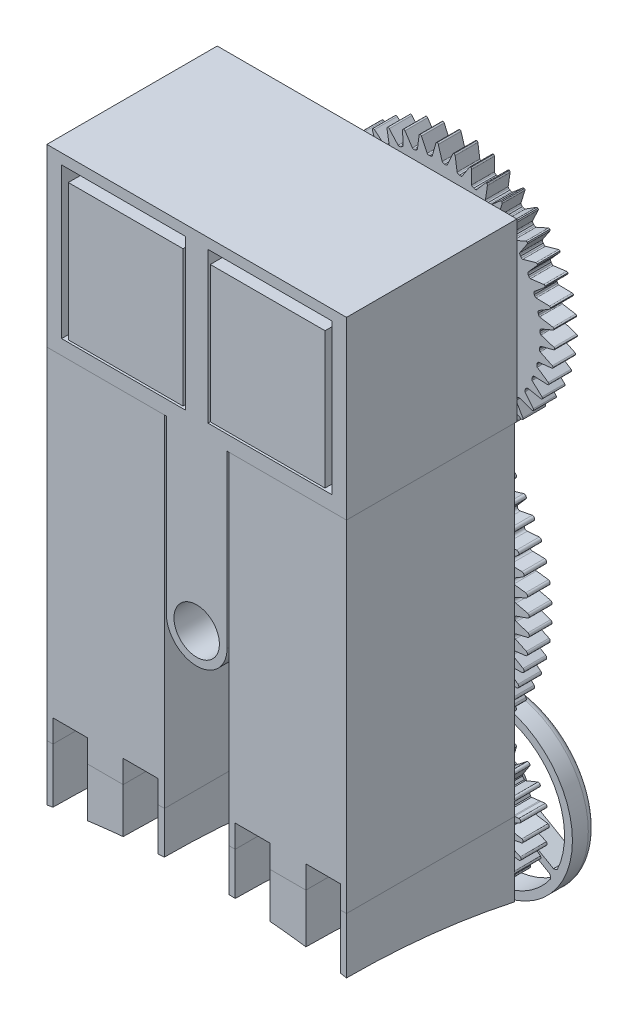
SolidWorks part; units mm, degrees
ref_plane "前视基准面" through (0, 0, 0) normal (0, 0, 1) x (1, 0, 0)
ref_plane "上视基准面" through (0, 0, 0) normal (0, 1, 0) x (1, 0, 0)
ref_plane "右视基准面" through (0, 0, 0) normal (1, 0, 0) x (0, 0, -1)
sketch "草图1" plane through (0, 0, 0) normal (0, 0, 1) x (1, 0, 0)
  line L52 (13.1903, 14.1616) -> (13.1903, -1.2939)
  line L75 (13.1903, 14.1616) -> (-13.1903, 14.1616)
  line L77 (13.1903, -1.2939) -> (2.6743, -1.2939)
  line L78 (-13.1903, 14.1616) -> (-13.1903, -1.2939)
  line L79 (-11.8944, 13.2473) -> (-0.9867, 13.2473)
  line L80 (-11.8944, 13.2473) -> (-11.8944, 0)
  line L81 (-11.8944, 0) -> (-0.9867, 0)
  line L82 (-0.9867, 13.2473) -> (-0.9867, 0)
  line L83 (11.8944, 0) -> (0.9867, 0)
  line L84 (0.9867, 13.2473) -> (0.9867, 0)
  line L85 (11.8944, 13.2473) -> (0.9867, 13.2473)
  line L86 (11.8944, 13.2473) -> (11.8944, 0)
  line L87 (-2.6743, -16.3459) -> (-2.6743, -1.2939)
  line L88 (2.6743, -16.3459) -> (2.6743, -1.2939)
  line L89 (-2.6743, -1.2939) -> (-13.1903, -1.2939)
  circle A0 centre (0, -16.3459) radius 2
  arc A1 (-2.6743, -16.3459) -> (2.6743, -16.3459) centre (0, -16.3459) ccw
  point P8 (-1.6019, -21.082)
  dimension "D5" = 4
extrude "凸台-拉伸1" add sketch "草图1" along normal blind 15
sketch "草图5" plane through (0, 0, 0) normal (0, 0, 1) x (1, 0, 0)
  line L0 (-11.3, 12.2) -> (-11.3, 0.2)
  line L5 (-11.3, 0.2) -> (-1.2, 0.2)
  line L6 (-1.2, 12.2) -> (-1.2, 0.2)
  line L7 (-11.3, 12.2) -> (-1.2, 12.2)
  line L9 (11.3, 12.2) -> (1.2, 12.2)
  line L10 (1.2, 12.2) -> (1.2, 0.2)
  line L11 (11.3, 0.2) -> (1.2, 0.2)
  line L12 (11.3, 12.2) -> (11.3, 0.2)
extrude "凸台-拉伸2" add sketch "草图5" along normal blind 15 separate body
sketch "草图6" plane through (0, 0, 0) normal (0, 0, -1) x (-1, 0, 0)
  line L5 (0.5574, -2.1882) -> (0.2083, -3.1894)
  line L6 (-0.5574, -2.1882) -> (-0.2083, -3.1894)
  line L7 (0.9255, -2.2075) -> (1.1681, -3.2397)
  line L9 (-0.9255, -2.2075) -> (-1.1681, -3.2397)
  line L10 (2.0343, -2.324) -> (1.5824, -3.2833)
  line L11 (2.3983, -2.3816) -> (2.5316, -3.4336)
  line L12 (3.4888, -2.6134) -> (2.9391, -3.5202)
  line L13 (3.8448, -2.7088) -> (3.8675, -3.769)
  line L14 (4.9051, -3.0534) -> (4.2637, -3.8977)
  line L15 (5.2492, -3.1854) -> (5.1609, -4.2421)
  line L16 (6.2677, -3.6389) -> (5.5415, -4.4116)
  line L17 (6.5961, -3.8062) -> (6.3978, -4.8479)
  line L18 (7.5616, -4.3637) -> (6.7586, -5.0562)
  line L19 (7.8707, -4.5644) -> (7.5647, -5.5797)
  line L20 (8.7727, -5.2197) -> (7.9017, -5.8245)
  line L21 (9.0591, -5.4517) -> (8.6486, -6.4294)
  line L22 (9.8876, -6.1977) -> (8.9582, -6.7081)
  line L23 (10.1483, -6.4583) -> (9.6378, -7.3877)
  line L24 (10.8943, -7.2868) -> (9.9166, -7.6973)
  line L25 (11.1262, -7.5732) -> (10.5214, -8.4442)
  line L26 (11.7815, -8.4752) -> (10.7663, -8.7813)
  line L27 (11.9823, -8.7843) -> (11.2897, -9.5873)
  line L28 (12.5397, -9.7498) -> (11.498, -9.9481)
  line L29 (12.707, -10.0782) -> (11.9343, -10.8044)
  line L30 (13.1605, -11.0967) -> (12.1038, -11.185)
  line L31 (13.2926, -11.4408) -> (12.4482, -12.0822)
  line L32 (13.6371, -12.5011) -> (12.5769, -12.4785)
  line L33 (13.7325, -12.8571) -> (12.8257, -13.4068)
  line L34 (13.9643, -13.9476) -> (12.9123, -13.8143)
  line L35 (14.0219, -14.3116) -> (13.0626, -14.7635)
  line L36 (14.1385, -15.4204) -> (13.1062, -15.1779)
  line L37 (14.1578, -15.7885) -> (13.1565, -16.1376)
  line L38 (14.1578, -16.9034) -> (13.1565, -16.5542)
  line L39 (14.1385, -17.2714) -> (13.1062, -17.514)
  line L40 (14.0219, -18.3802) -> (13.0626, -17.9283)
  line L41 (13.9643, -18.7442) -> (12.9123, -18.8776)
  line L42 (13.7325, -19.8347) -> (12.8257, -19.2851)
  line L43 (13.6371, -20.1907) -> (12.5769, -20.2134)
  line L44 (13.2926, -21.2511) -> (12.4482, -20.6096)
  line L45 (13.1605, -21.5951) -> (12.1038, -21.5068)
  line L46 (12.707, -22.6136) -> (11.9343, -21.8874)
  line L47 (12.5397, -22.942) -> (11.498, -22.7438)
  line L48 (11.9823, -23.9076) -> (11.2897, -23.1046)
  line L49 (11.7815, -24.2167) -> (10.7663, -23.9106)
  line L50 (11.1262, -25.1186) -> (10.5214, -24.2476)
  line L51 (10.8943, -25.405) -> (9.9166, -24.9945)
  line L52 (10.1483, -26.2336) -> (9.6378, -25.3041)
  line L53 (9.8876, -26.4942) -> (8.9582, -25.9837)
  line L54 (9.0591, -27.2402) -> (8.6486, -26.2625)
  line L55 (8.7727, -27.4721) -> (7.9017, -26.8673)
  line L56 (7.8707, -28.1274) -> (7.5647, -27.1122)
  line L57 (7.5616, -28.3282) -> (6.7586, -27.6356)
  line L58 (6.5961, -28.8856) -> (6.3978, -27.8439)
  line L59 (6.2677, -29.0529) -> (5.5415, -28.2802)
  line L60 (5.2492, -29.5064) -> (5.1609, -28.4497)
  line L61 (4.9051, -29.6385) -> (4.2637, -28.7941)
  line L62 (3.8448, -29.983) -> (3.8675, -28.9229)
  line L63 (3.4888, -30.0784) -> (2.9391, -29.1716)
  line L64 (2.3983, -30.3102) -> (2.5316, -29.2582)
  line L65 (2.0343, -30.3678) -> (1.5824, -29.4086)
  line L66 (0.9255, -30.4844) -> (1.1681, -29.4521)
  line L67 (0.5574, -30.5037) -> (0.2083, -29.5024)
  line L68 (-0.5574, -30.5037) -> (-0.2083, -29.5024)
  line L69 (-0.9255, -30.4844) -> (-1.1681, -29.4521)
  line L70 (-2.0343, -30.3678) -> (-1.5824, -29.4086)
  line L71 (-2.3983, -30.3102) -> (-2.5316, -29.2582)
  line L72 (-3.4888, -30.0784) -> (-2.9391, -29.1716)
  line L73 (-3.8448, -29.983) -> (-3.8675, -28.9229)
  line L74 (-4.9051, -29.6385) -> (-4.2637, -28.7941)
  line L75 (-5.2492, -29.5064) -> (-5.1609, -28.4497)
  line L76 (-6.2677, -29.0529) -> (-5.5415, -28.2802)
  line L77 (-6.5961, -28.8856) -> (-6.3978, -27.8439)
  line L78 (-7.5616, -28.3282) -> (-6.7586, -27.6356)
  line L79 (-7.8707, -28.1274) -> (-7.5647, -27.1122)
  line L80 (-8.7727, -27.4721) -> (-7.9017, -26.8673)
  line L81 (-9.0591, -27.2402) -> (-8.6486, -26.2625)
  line L82 (-9.8876, -26.4942) -> (-8.9582, -25.9837)
  line L83 (-10.1483, -26.2336) -> (-9.6378, -25.3041)
  line L84 (-10.8943, -25.405) -> (-9.9166, -24.9945)
  line L85 (-11.1262, -25.1186) -> (-10.5214, -24.2476)
  line L86 (-11.7815, -24.2167) -> (-10.7663, -23.9106)
  line L87 (-11.9823, -23.9076) -> (-11.2897, -23.1046)
  line L88 (-12.5397, -22.942) -> (-11.498, -22.7438)
  line L89 (-12.707, -22.6136) -> (-11.9343, -21.8874)
  line L90 (-13.1605, -21.5951) -> (-12.1038, -21.5068)
  line L91 (-13.2926, -21.2511) -> (-12.4482, -20.6096)
  line L92 (-13.6371, -20.1907) -> (-12.5769, -20.2134)
  line L93 (-13.7325, -19.8347) -> (-12.8257, -19.2851)
  line L94 (-13.9643, -18.7442) -> (-12.9123, -18.8776)
  line L95 (-14.0219, -18.3802) -> (-13.0626, -17.9283)
  line L96 (-14.1385, -17.2714) -> (-13.1062, -17.514)
  line L97 (-14.1578, -16.9034) -> (-13.1565, -16.5542)
  line L98 (-14.1578, -15.7885) -> (-13.1565, -16.1376)
  line L99 (-14.1385, -15.4204) -> (-13.1062, -15.1779)
  line L100 (-14.0219, -14.3116) -> (-13.0626, -14.7635)
  line L101 (-13.9643, -13.9476) -> (-12.9123, -13.8143)
  line L102 (-13.7325, -12.8571) -> (-12.8257, -13.4068)
  line L103 (-13.6371, -12.5011) -> (-12.5769, -12.4785)
  line L104 (-13.2926, -11.4408) -> (-12.4482, -12.0822)
  line L105 (-13.1605, -11.0967) -> (-12.1038, -11.185)
  line L106 (-12.707, -10.0782) -> (-11.9343, -10.8044)
  line L107 (-12.5397, -9.7498) -> (-11.498, -9.9481)
  line L108 (-11.9823, -8.7843) -> (-11.2897, -9.5873)
  line L109 (-11.7815, -8.4752) -> (-10.7663, -8.7813)
  line L110 (-11.1262, -7.5732) -> (-10.5214, -8.4442)
  line L111 (-10.8943, -7.2868) -> (-9.9166, -7.6973)
  line L112 (-10.1483, -6.4583) -> (-9.6378, -7.3877)
  line L113 (-9.8876, -6.1977) -> (-8.9582, -6.7081)
  line L114 (-9.0591, -5.4517) -> (-8.6486, -6.4294)
  line L115 (-8.7727, -5.2197) -> (-7.9017, -5.8245)
  line L116 (-7.8707, -4.5644) -> (-7.5647, -5.5797)
  line L117 (-7.5616, -4.3637) -> (-6.7586, -5.0562)
  line L118 (-6.5961, -3.8062) -> (-6.3978, -4.8479)
  line L119 (-6.2677, -3.6389) -> (-5.5415, -4.4116)
  line L120 (-5.2492, -3.1854) -> (-5.1609, -4.2421)
  line L121 (-4.9051, -3.0534) -> (-4.2637, -3.8977)
  line L122 (-3.8448, -2.7088) -> (-3.8675, -3.769)
  line L123 (-3.4888, -2.6134) -> (-2.9391, -3.5202)
  line L124 (-2.3983, -2.3816) -> (-2.5316, -3.4336)
  line L125 (-2.0343, -2.324) -> (-1.5824, -3.2833)
  arc A1 (-1.3589, -3.4171) -> (-1.1681, -3.2397) centre (-1.3815, -3.2014) ccw
  arc A2 (-0.9255, -2.2075) -> (-0.5574, -2.1882) centre (-0.7383, -2.2588) cw
  arc A3 (0, -3.3459) -> (-0.2083, -3.1894) centre (0, -3.129) cw
  arc A4 (0, -3.3459) -> (0.2083, -3.1894) centre (0, -3.129) ccw
  arc A5 (1.3589, -3.4171) -> (1.1681, -3.2397) centre (1.3815, -3.2014) cw
  arc A6 (0.5574, -2.1882) -> (0.9255, -2.2075) centre (0.7383, -2.2588) cw
  arc A7 (1.3589, -3.4171) -> (1.5824, -3.2833) centre (1.3815, -3.2014) ccw
  arc A8 (2.7029, -3.63) -> (2.5316, -3.4336) centre (2.7479, -3.4179) cw
  arc A9 (2.0343, -2.324) -> (2.3983, -2.3816) centre (2.2067, -2.4131) cw
  arc A10 (2.7029, -3.63) -> (2.9391, -3.5202) centre (2.7479, -3.4179) ccw
  arc A11 (4.0172, -3.9822) -> (3.8675, -3.769) centre (4.0842, -3.7759) cw
  arc A12 (3.4888, -2.6134) -> (3.8448, -2.7088) centre (3.651, -2.7201) cw
  arc A13 (4.0172, -3.9822) -> (4.2637, -3.8977) centre (4.0842, -3.7759) ccw
  arc A14 (5.2876, -4.4698) -> (5.1609, -4.2421) centre (5.3758, -4.2717) cw
  arc A15 (4.9051, -3.0534) -> (5.2492, -3.1854) centre (5.0553, -3.1764) cw
  arc A16 (5.2876, -4.4698) -> (5.5415, -4.4116) centre (5.3758, -4.2717) ccw
  arc A17 (6.5, -5.0876) -> (6.3978, -4.8479) centre (6.6084, -4.8998) cw
  arc A18 (6.2677, -3.6389) -> (6.5961, -3.8062) centre (6.4042, -3.7769) cw
  arc A19 (6.5, -5.0876) -> (6.7586, -5.0562) centre (6.6084, -4.8998) ccw
  arc A20 (7.6412, -5.8287) -> (7.5647, -5.5797) centre (7.7687, -5.6532) cw
  arc A21 (7.5616, -4.3637) -> (7.8707, -4.5644) centre (7.6829, -4.5152) cw
  arc A22 (7.6412, -5.8287) -> (7.9017, -5.8245) centre (7.7687, -5.6532) ccw
  arc A23 (8.6987, -6.685) -> (8.6486, -6.4294) centre (8.8438, -6.5239) cw
  arc A24 (8.7727, -5.2197) -> (9.0591, -5.4517) centre (8.8775, -5.3831) cw
  arc A25 (8.6987, -6.685) -> (8.9582, -6.7081) centre (8.8438, -6.5239) ccw
  arc A26 (9.6609, -7.6472) -> (9.6378, -7.3877) centre (9.8221, -7.5021) cw
  arc A27 (9.8876, -6.1977) -> (10.1483, -6.4583) centre (9.9748, -6.3711) cw
  arc A28 (9.6609, -7.6472) -> (9.9166, -7.6973) centre (9.8221, -7.5021) ccw
  arc A29 (10.5172, -8.7047) -> (10.5214, -8.4442) centre (10.6927, -8.5772) cw
  arc A30 (10.8943, -7.2868) -> (11.1262, -7.5732) centre (10.9628, -7.4684) cw
  arc A31 (10.5172, -8.7047) -> (10.7663, -8.7813) centre (10.6927, -8.5772) ccw
  arc A32 (11.2583, -9.8459) -> (11.2897, -9.5873) centre (11.4462, -9.7375) cw
  arc A33 (11.7815, -8.4752) -> (11.9823, -8.7843) centre (11.8307, -8.663) cw
  arc A34 (11.2583, -9.8459) -> (11.498, -9.9481) centre (11.4462, -9.7375) ccw
  arc A35 (11.8761, -11.0583) -> (11.9343, -10.8044) centre (12.0742, -10.9701) cw
  arc A36 (12.5397, -9.7498) -> (12.707, -10.0782) centre (12.569, -9.9417) cw
  arc A37 (11.8761, -11.0583) -> (12.1038, -11.185) centre (12.0742, -10.9701) ccw
  arc A38 (12.3637, -12.3287) -> (12.4482, -12.0822) centre (12.57, -12.2617) cw
  arc A39 (13.1605, -11.0967) -> (13.2926, -11.4408) centre (13.1695, -11.2906) cw
  arc A40 (12.3637, -12.3287) -> (12.5769, -12.4785) centre (12.57, -12.2617) ccw
  arc A41 (12.7159, -13.6431) -> (12.8257, -13.4068) centre (12.9281, -13.598) cw
  arc A42 (13.6371, -12.5011) -> (13.7325, -12.8571) centre (13.6258, -12.6949) cw
  arc A43 (12.7159, -13.6431) -> (12.9123, -13.8143) centre (12.9281, -13.598) ccw
  arc A44 (12.9288, -14.987) -> (13.0626, -14.7635) centre (13.1445, -14.9644) cw
  arc A45 (13.9643, -13.9476) -> (14.0219, -14.3116) centre (13.9328, -14.1392) cw
  arc A46 (12.9288, -14.987) -> (13.1062, -15.1779) centre (13.1445, -14.9644) ccw
  arc A47 (13, -16.3459) -> (13.1565, -16.1376) centre (13.2169, -16.3459) cw
  arc A48 (14.1385, -15.4204) -> (14.1578, -15.7885) centre (14.0872, -15.6076) cw
  arc A49 (13, -16.3459) -> (13.1565, -16.5542) centre (13.2169, -16.3459) ccw
  arc A50 (12.9288, -17.7048) -> (13.1062, -17.514) centre (13.1445, -17.7275) cw
  arc A51 (14.1578, -16.9034) -> (14.1385, -17.2714) centre (14.0872, -17.0842) cw
  arc A52 (12.9288, -17.7048) -> (13.0626, -17.9283) centre (13.1445, -17.7275) ccw
  arc A53 (12.7159, -19.0488) -> (12.9123, -18.8776) centre (12.9281, -19.0939) cw
  arc A54 (14.0219, -18.3802) -> (13.9643, -18.7442) centre (13.9328, -18.5527) cw
  arc A55 (12.7159, -19.0488) -> (12.8257, -19.2851) centre (12.9281, -19.0939) ccw
  arc A56 (12.3637, -20.3631) -> (12.5769, -20.2134) centre (12.57, -20.4302) cw
  arc A57 (13.7325, -19.8347) -> (13.6371, -20.1907) centre (13.6258, -19.9969) cw
  arc A58 (12.3637, -20.3631) -> (12.4482, -20.6096) centre (12.57, -20.4302) ccw
  arc A59 (11.8761, -21.6335) -> (12.1038, -21.5068) centre (12.0742, -21.7217) cw
  arc A60 (13.2926, -21.2511) -> (13.1605, -21.5951) centre (13.1695, -21.4012) cw
  arc A61 (11.8761, -21.6335) -> (11.9343, -21.8874) centre (12.0742, -21.7217) ccw
  arc A62 (11.2583, -22.8459) -> (11.498, -22.7438) centre (11.4462, -22.9544) cw
  arc A63 (12.707, -22.6136) -> (12.5397, -22.942) centre (12.569, -22.7501) cw
  arc A64 (11.2583, -22.8459) -> (11.2897, -23.1046) centre (11.4462, -22.9544) ccw
  arc A65 (10.5172, -23.9871) -> (10.7663, -23.9106) centre (10.6927, -24.1146) cw
  arc A66 (11.9823, -23.9076) -> (11.7815, -24.2167) centre (11.8307, -24.0289) cw
  arc A67 (10.5172, -23.9871) -> (10.5214, -24.2476) centre (10.6927, -24.1146) ccw
  arc A68 (9.6609, -25.0446) -> (9.9166, -24.9945) centre (9.8221, -25.1897) cw
  arc A69 (11.1262, -25.1186) -> (10.8943, -25.405) centre (10.9628, -25.2234) cw
  arc A70 (9.6609, -25.0446) -> (9.6378, -25.3041) centre (9.8221, -25.1897) ccw
  arc A71 (8.6987, -26.0068) -> (8.9582, -25.9837) centre (8.8438, -26.168) cw
  arc A72 (10.1483, -26.2336) -> (9.8876, -26.4942) centre (9.9748, -26.3207) cw
  arc A73 (8.6987, -26.0068) -> (8.6486, -26.2625) centre (8.8438, -26.168) ccw
  arc A74 (7.6412, -26.8631) -> (7.9017, -26.8673) centre (7.7687, -27.0386) cw
  arc A75 (9.0591, -27.2402) -> (8.7727, -27.4721) centre (8.8775, -27.3087) cw
  arc A76 (7.6412, -26.8631) -> (7.5647, -27.1122) centre (7.7687, -27.0386) ccw
  arc A77 (6.5, -27.6043) -> (6.7586, -27.6356) centre (6.6084, -27.7921) cw
  arc A78 (7.8707, -28.1274) -> (7.5616, -28.3282) centre (7.6829, -28.1766) cw
  arc A79 (6.5, -27.6043) -> (6.3978, -27.8439) centre (6.6084, -27.7921) ccw
  arc A80 (5.2876, -28.222) -> (5.5415, -28.2802) centre (5.3758, -28.4201) cw
  arc A81 (6.5961, -28.8856) -> (6.2677, -29.0529) centre (6.4042, -28.9149) cw
  arc A82 (5.2876, -28.222) -> (5.1609, -28.4497) centre (5.3758, -28.4201) ccw
  arc A83 (4.0172, -28.7097) -> (4.2637, -28.7941) centre (4.0842, -28.9159) cw
  arc A84 (5.2492, -29.5064) -> (4.9051, -29.6385) centre (5.0553, -29.5155) cw
  arc A85 (4.0172, -28.7097) -> (3.8675, -28.9229) centre (4.0842, -28.9159) ccw
  arc A86 (2.7029, -29.0618) -> (2.9391, -29.1716) centre (2.7479, -29.274) cw
  arc A87 (3.8448, -29.983) -> (3.4888, -30.0784) centre (3.651, -29.9717) cw
  arc A88 (2.7029, -29.0618) -> (2.5316, -29.2582) centre (2.7479, -29.274) ccw
  arc A89 (1.3589, -29.2747) -> (1.5824, -29.4086) centre (1.3815, -29.4904) cw
  arc A90 (2.3983, -30.3102) -> (2.0343, -30.3678) centre (2.2067, -30.2787) cw
  arc A91 (1.3589, -29.2747) -> (1.1681, -29.4521) centre (1.3815, -29.4904) ccw
  arc A92 (0, -29.3459) -> (0.2083, -29.5024) centre (0, -29.5628) cw
  arc A93 (0.9255, -30.4844) -> (0.5574, -30.5037) centre (0.7383, -30.4331) cw
  arc A94 (0, -29.3459) -> (-0.2083, -29.5024) centre (0, -29.5628) ccw
  arc A95 (-1.3589, -29.2747) -> (-1.1681, -29.4521) centre (-1.3815, -29.4904) cw
  arc A96 (-0.5574, -30.5037) -> (-0.9255, -30.4844) centre (-0.7383, -30.4331) cw
  arc A97 (-1.3589, -29.2747) -> (-1.5824, -29.4086) centre (-1.3815, -29.4904) ccw
  arc A98 (-2.7029, -29.0618) -> (-2.5316, -29.2582) centre (-2.7479, -29.274) cw
  arc A99 (-2.0343, -30.3678) -> (-2.3983, -30.3102) centre (-2.2067, -30.2787) cw
  arc A100 (-2.7029, -29.0618) -> (-2.9391, -29.1716) centre (-2.7479, -29.274) ccw
  arc A101 (-4.0172, -28.7097) -> (-3.8675, -28.9229) centre (-4.0842, -28.9159) cw
  arc A102 (-3.4888, -30.0784) -> (-3.8448, -29.983) centre (-3.651, -29.9717) cw
  arc A103 (-4.0172, -28.7097) -> (-4.2637, -28.7941) centre (-4.0842, -28.9159) ccw
  arc A104 (-5.2876, -28.222) -> (-5.1609, -28.4497) centre (-5.3758, -28.4201) cw
  arc A105 (-4.9051, -29.6385) -> (-5.2492, -29.5064) centre (-5.0553, -29.5155) cw
  arc A106 (-5.2876, -28.222) -> (-5.5415, -28.2802) centre (-5.3758, -28.4201) ccw
  arc A107 (-6.5, -27.6043) -> (-6.3978, -27.8439) centre (-6.6084, -27.7921) cw
  arc A108 (-6.2677, -29.0529) -> (-6.5961, -28.8856) centre (-6.4042, -28.9149) cw
  arc A109 (-6.5, -27.6043) -> (-6.7586, -27.6356) centre (-6.6084, -27.7921) ccw
  arc A110 (-7.6412, -26.8631) -> (-7.5647, -27.1122) centre (-7.7687, -27.0386) cw
  arc A111 (-7.5616, -28.3282) -> (-7.8707, -28.1274) centre (-7.6829, -28.1766) cw
  arc A112 (-7.6412, -26.8631) -> (-7.9017, -26.8673) centre (-7.7687, -27.0386) ccw
  arc A113 (-8.6987, -26.0068) -> (-8.6486, -26.2625) centre (-8.8438, -26.168) cw
  arc A114 (-8.7727, -27.4721) -> (-9.0591, -27.2402) centre (-8.8775, -27.3087) cw
  arc A115 (-8.6987, -26.0068) -> (-8.9582, -25.9837) centre (-8.8438, -26.168) ccw
  arc A116 (-9.6609, -25.0446) -> (-9.6378, -25.3041) centre (-9.8221, -25.1897) cw
  arc A117 (-9.8876, -26.4942) -> (-10.1483, -26.2336) centre (-9.9748, -26.3207) cw
  arc A118 (-9.6609, -25.0446) -> (-9.9166, -24.9945) centre (-9.8221, -25.1897) ccw
  arc A119 (-10.5172, -23.9871) -> (-10.5214, -24.2476) centre (-10.6927, -24.1146) cw
  arc A120 (-10.8943, -25.405) -> (-11.1262, -25.1186) centre (-10.9628, -25.2234) cw
  arc A121 (-10.5172, -23.9871) -> (-10.7663, -23.9106) centre (-10.6927, -24.1146) ccw
  arc A122 (-11.2583, -22.8459) -> (-11.2897, -23.1046) centre (-11.4462, -22.9544) cw
  arc A123 (-11.7815, -24.2167) -> (-11.9823, -23.9076) centre (-11.8307, -24.0289) cw
  arc A124 (-11.2583, -22.8459) -> (-11.498, -22.7438) centre (-11.4462, -22.9544) ccw
  arc A125 (-11.8761, -21.6335) -> (-11.9343, -21.8874) centre (-12.0742, -21.7217) cw
  arc A126 (-12.5397, -22.942) -> (-12.707, -22.6136) centre (-12.569, -22.7501) cw
  arc A127 (-11.8761, -21.6335) -> (-12.1038, -21.5068) centre (-12.0742, -21.7217) ccw
  arc A128 (-12.3637, -20.3631) -> (-12.4482, -20.6096) centre (-12.57, -20.4302) cw
  arc A129 (-13.1605, -21.5951) -> (-13.2926, -21.2511) centre (-13.1695, -21.4012) cw
  arc A130 (-12.3637, -20.3631) -> (-12.5769, -20.2134) centre (-12.57, -20.4302) ccw
  arc A131 (-12.7159, -19.0488) -> (-12.8257, -19.2851) centre (-12.9281, -19.0939) cw
  arc A132 (-13.6371, -20.1907) -> (-13.7325, -19.8347) centre (-13.6258, -19.9969) cw
  arc A133 (-12.7159, -19.0488) -> (-12.9123, -18.8776) centre (-12.9281, -19.0939) ccw
  arc A134 (-12.9288, -17.7048) -> (-13.0626, -17.9283) centre (-13.1445, -17.7275) cw
  arc A135 (-13.9643, -18.7442) -> (-14.0219, -18.3802) centre (-13.9328, -18.5527) cw
  arc A136 (-12.9288, -17.7048) -> (-13.1062, -17.514) centre (-13.1445, -17.7275) ccw
  arc A137 (-13, -16.3459) -> (-13.1565, -16.5542) centre (-13.2169, -16.3459) cw
  arc A138 (-14.1385, -17.2714) -> (-14.1578, -16.9034) centre (-14.0872, -17.0842) cw
  arc A139 (-13, -16.3459) -> (-13.1565, -16.1376) centre (-13.2169, -16.3459) ccw
  arc A140 (-12.9288, -14.987) -> (-13.1062, -15.1779) centre (-13.1445, -14.9644) cw
  arc A141 (-14.1578, -15.7885) -> (-14.1385, -15.4204) centre (-14.0872, -15.6076) cw
  arc A142 (-12.9288, -14.987) -> (-13.0626, -14.7635) centre (-13.1445, -14.9644) ccw
  arc A143 (-12.7159, -13.6431) -> (-12.9123, -13.8143) centre (-12.9281, -13.598) cw
  arc A144 (-14.0219, -14.3116) -> (-13.9643, -13.9476) centre (-13.9328, -14.1392) cw
  arc A145 (-12.7159, -13.6431) -> (-12.8257, -13.4068) centre (-12.9281, -13.598) ccw
  arc A146 (-12.3637, -12.3287) -> (-12.5769, -12.4785) centre (-12.57, -12.2617) cw
  arc A147 (-13.7325, -12.8571) -> (-13.6371, -12.5011) centre (-13.6258, -12.6949) cw
  arc A148 (-12.3637, -12.3287) -> (-12.4482, -12.0822) centre (-12.57, -12.2617) ccw
  arc A149 (-11.8761, -11.0583) -> (-12.1038, -11.185) centre (-12.0742, -10.9701) cw
  arc A150 (-13.2926, -11.4408) -> (-13.1605, -11.0967) centre (-13.1695, -11.2906) cw
  arc A151 (-11.8761, -11.0583) -> (-11.9343, -10.8044) centre (-12.0742, -10.9701) ccw
  arc A152 (-11.2583, -9.8459) -> (-11.498, -9.9481) centre (-11.4462, -9.7375) cw
  arc A153 (-12.707, -10.0782) -> (-12.5397, -9.7498) centre (-12.569, -9.9417) cw
  arc A154 (-11.2583, -9.8459) -> (-11.2897, -9.5873) centre (-11.4462, -9.7375) ccw
  arc A155 (-10.5172, -8.7047) -> (-10.7663, -8.7813) centre (-10.6927, -8.5772) cw
  arc A156 (-11.9823, -8.7843) -> (-11.7815, -8.4752) centre (-11.8307, -8.663) cw
  arc A157 (-10.5172, -8.7047) -> (-10.5214, -8.4442) centre (-10.6927, -8.5772) ccw
  arc A158 (-9.6609, -7.6472) -> (-9.9166, -7.6973) centre (-9.8221, -7.5021) cw
  arc A159 (-11.1262, -7.5732) -> (-10.8943, -7.2868) centre (-10.9628, -7.4684) cw
  arc A160 (-9.6609, -7.6472) -> (-9.6378, -7.3877) centre (-9.8221, -7.5021) ccw
  arc A161 (-8.6987, -6.685) -> (-8.9582, -6.7081) centre (-8.8438, -6.5239) cw
  arc A162 (-10.1483, -6.4583) -> (-9.8876, -6.1977) centre (-9.9748, -6.3711) cw
  arc A163 (-8.6987, -6.685) -> (-8.6486, -6.4294) centre (-8.8438, -6.5239) ccw
  arc A164 (-7.6412, -5.8287) -> (-7.9017, -5.8245) centre (-7.7687, -5.6532) cw
  arc A165 (-9.0591, -5.4517) -> (-8.7727, -5.2197) centre (-8.8775, -5.3831) cw
  arc A166 (-7.6412, -5.8287) -> (-7.5647, -5.5797) centre (-7.7687, -5.6532) ccw
  arc A167 (-6.5, -5.0876) -> (-6.7586, -5.0562) centre (-6.6084, -4.8998) cw
  arc A168 (-7.8707, -4.5644) -> (-7.5616, -4.3637) centre (-7.6829, -4.5152) cw
  arc A169 (-6.5, -5.0876) -> (-6.3978, -4.8479) centre (-6.6084, -4.8998) ccw
  arc A170 (-5.2876, -4.4698) -> (-5.5415, -4.4116) centre (-5.3758, -4.2717) cw
  arc A171 (-6.5961, -3.8062) -> (-6.2677, -3.6389) centre (-6.4042, -3.7769) cw
  arc A172 (-5.2876, -4.4698) -> (-5.1609, -4.2421) centre (-5.3758, -4.2717) ccw
  arc A173 (-4.0172, -3.9822) -> (-4.2637, -3.8977) centre (-4.0842, -3.7759) cw
  arc A174 (-5.2492, -3.1854) -> (-4.9051, -3.0534) centre (-5.0553, -3.1764) cw
  arc A175 (-4.0172, -3.9822) -> (-3.8675, -3.769) centre (-4.0842, -3.7759) ccw
  arc A176 (-2.7029, -3.63) -> (-2.9391, -3.5202) centre (-2.7479, -3.4179) cw
  arc A177 (-3.8448, -2.7088) -> (-3.4888, -2.6134) centre (-3.651, -2.7201) cw
  arc A178 (-2.7029, -3.63) -> (-2.5316, -3.4336) centre (-2.7479, -3.4179) ccw
  arc A179 (-1.3589, -3.4171) -> (-1.5824, -3.2833) centre (-1.3815, -3.2014) cw
  arc A180 (-2.3983, -2.3816) -> (-2.0343, -2.324) centre (-2.2067, -2.4131) cw
  circle A181 centre (0, -16.3459) radius 2
  point P545 (0, -16.3459)
  dimension "D2" = 60
extrude "凸台-拉伸6" add sketch "草图6" along normal blind 2 separate body
sketch "草图7" plane through (0, 0, 0) normal (0, 0, -1) x (-1, 0, 0)
  line L0 (-11.3, 6.2) -> (-1.2, 6.2)
  line L1 (-11.3, 0.2) -> (-11.3, 12.2) construction
  line L2 (-1.2, 12.2) -> (-1.2, 0.2) construction
  line L3 (-4.7758, -2.747) -> (-4.2184, -3.7844)
  line L4 (-4.8878, -2.6931) -> (-5.0141, -2.6931)
  line L6 (-3.9278, -2.5652) -> (-4.0111, -3.74)
  line L7 (-3.8477, -2.4702) -> (-3.7325, -2.4184)
  line L8 (-6.0942, -2.8663) -> (-5.6938, -3.9738)
  line L9 (-5.2288, -2.8099) -> (-5.4822, -3.96)
  line L10 (-6.1972, -2.7967) -> (-6.3222, -2.7783)
  line L11 (-5.1357, -2.7276) -> (-5.0141, -2.6931)
  line L12 (-7.4159, -2.7924) -> (-7.181, -3.9464)
  line L13 (-6.5516, -2.8626) -> (-6.9697, -3.9636)
  line L14 (-7.5077, -2.7085) -> (-7.6286, -2.6721)
  line L15 (-6.4474, -2.7947) -> (-6.3222, -2.7783)
  line L16 (-8.7128, -2.5268) -> (-8.6484, -3.7027)
  line L17 (-7.8679, -2.7221) -> (-8.4419, -3.7505)
  line L18 (-8.7913, -2.4305) -> (-8.9057, -2.3768)
  line L19 (-7.755, -2.6701) -> (-7.6286, -2.6721)
  line L20 (-9.9571, -2.0752) -> (-10.0647, -3.248)
  line L21 (-9.1497, -2.3915) -> (-9.8673, -3.3253)
  line L22 (-10.0209, -1.9685) -> (-10.1262, -1.8988)
  line L23 (-9.0304, -2.3564) -> (-8.9057, -2.3768)
  line L24 (-11.1225, -1.4473) -> (-11.3997, -2.5919)
  line L25 (-10.3697, -1.8777) -> (-11.2157, -2.6971)
  line L26 (-11.17, -1.3324) -> (-11.2641, -1.2481)
  line L27 (-10.2466, -1.8604) -> (-10.1262, -1.8988)
  line L28 (-12.184, -0.6563) -> (-12.6249, -1.7484)
  line L29 (-11.502, -1.1918) -> (-12.4582, -1.8793)
  line L30 (-12.2143, -0.5358) -> (-12.2951, -0.4386)
  line L31 (-11.3776, -1.1926) -> (-11.2641, -1.2481)
  line L32 (-13.1191, 0.2808) -> (-13.7143, -0.7355)
  line L33 (-12.5222, -0.3484) -> (-13.5684, -0.8893)
  line L34 (-13.1315, 0.4044) -> (-13.1973, 0.5123)
  line L35 (-12.3994, -0.3672) -> (-12.2951, -0.4386)
  line L36 (-13.9077, 1.344) -> (-14.6445, 0.4252)
  line L37 (-13.4088, 0.6347) -> (-14.5226, 0.2519)
  line L38 (-13.902, 1.4682) -> (-13.9514, 1.5844)
  line L39 (-13.29, 0.5981) -> (-13.1973, 0.5123)
  line L40 (-14.5332, 2.5107) -> (-15.3959, 1.709)
  line L41 (-14.1429, 1.7363) -> (-15.3005, 1.5197)
  line L42 (-14.5094, 2.6327) -> (-14.5414, 2.755)
  line L43 (-14.0307, 1.6828) -> (-13.9514, 1.5844)
  line L44 (-14.9821, 3.7561) -> (-15.9523, 3.0885)
  line L45 (-14.7087, 2.9331) -> (-15.8855, 2.8874)
  line L46 (-14.9408, 3.8733) -> (-14.9546, 3.9989)
  line L47 (-14.6054, 2.8638) -> (-14.5414, 2.755)
  line L48 (-15.2449, 5.0535) -> (-16.3019, 4.5344)
  line L49 (-15.0942, 4.1995) -> (-16.2651, 4.3256)
  line L50 (-15.187, 5.1635) -> (-15.1823, 5.2898)
  line L51 (-15.0022, 4.116) -> (-14.9546, 3.9989)
  line L52 (-15.3159, 6.3754) -> (-16.4373, 6.0157)
  line L53 (-15.2912, 5.5086) -> (-16.4313, 5.8038)
  line L54 (-15.2426, 6.4758) -> (-15.2197, 6.6)
  line L55 (-15.2123, 5.4125) -> (-15.1823, 5.2898)
  line L56 (-15.1938, 7.6935) -> (-16.3556, 7.5009)
  line L57 (-15.2956, 6.8323) -> (-16.3805, 7.2904)
  line L58 (-15.1066, 7.7822) -> (-15.0659, 7.9018)
  line L59 (-15.2315, 6.7258) -> (-15.2197, 6.6)
  line L60 (-14.881, 8.9798) -> (-16.0585, 8.9585)
  line L61 (-15.1071, 8.1426) -> (-16.1138, 8.7538)
  line L62 (-14.7819, 9.0549) -> (-14.7241, 9.1672)
  line L63 (-15.0592, 8.0279) -> (-15.0659, 7.9018)
  line L64 (-14.3843, 10.2069) -> (-15.5523, 10.3572)
  line L65 (-14.7299, 9.4115) -> (-15.6368, 10.1628)
  line L66 (-14.2753, 10.2667) -> (-14.2018, 10.3694)
  line L67 (-14.6992, 9.2911) -> (-14.7241, 9.1672)
  line L68 (-13.7142, 11.3486) -> (-14.8479, 11.6673)
  line L69 (-14.1719, 10.612) -> (-14.9598, 11.4873)
  line L70 (-13.5977, 11.3918) -> (-13.51, 11.4828)
  line L71 (-14.1591, 10.4883) -> (-14.2018, 10.3694)
  line L72 (-12.885, 12.3805) -> (-13.9602, 12.8609)
  line L73 (-13.4451, 11.7184) -> (-14.0971, 12.6991)
  line L74 (-12.7634, 12.4063) -> (-12.6634, 12.4836)
  line L75 (-13.4504, 11.5942) -> (-13.51, 11.4828)
  line L76 (-11.9144, 13.2807) -> (-12.9082, 13.9126)
  line L77 (-12.5649, 12.7072) -> (-13.0672, 13.7724)
  line L78 (-11.7904, 13.2886) -> (-11.6802, 13.3504)
  line L79 (-12.5883, 12.5851) -> (-12.6634, 12.4836)
  line L80 (-10.8231, 14.03) -> (-11.7143, 14.7998)
  line L81 (-11.5502, 13.5573) -> (-11.892, 14.6843)
  line L82 (-10.6992, 14.0197) -> (-10.5812, 14.0648)
  line L83 (-11.591, 13.4399) -> (-11.6802, 13.3504)
  line L84 (-9.6343, 14.6124) -> (-10.4039, 15.5038)
  line L85 (-10.4224, 14.2506) -> (-10.5966, 15.4154)
  line L86 (-9.5132, 14.5842) -> (-9.3899, 14.6117)
  line L87 (-10.48, 14.1404) -> (-10.5812, 14.0648)
  line L88 (-8.3734, 15.0155) -> (-9.005, 16.0095)
  line L89 (-9.2058, 14.7724) -> (-9.2085, 15.95)
  line L90 (-8.2577, 14.97) -> (-8.1317, 14.9792)
  line L91 (-9.2788, 14.6717) -> (-9.3899, 14.6117)
  line L92 (-7.0672, 15.2307) -> (-7.5474, 16.3061)
  line L93 (-7.9261, 15.1114) -> (-7.7574, 16.2769)
  line L94 (-6.9594, 15.1688) -> (-6.8334, 15.1596)
  line L95 (-8.013, 15.0224) -> (-8.1317, 14.9792)
  line L96 (-5.7436, 15.2535) -> (-6.0621, 16.3873)
  line L97 (-6.6108, 15.2605) -> (-6.2741, 16.389)
  line L98 (-5.646, 15.1766) -> (-5.5227, 15.1491)
  line L99 (-6.7097, 15.1851) -> (-6.8334, 15.1596)
  line L100 (-4.4308, 15.0833) -> (-4.5808, 16.2514)
  line L101 (-5.2877, 15.2164) -> (-4.7903, 16.2839)
  line L102 (-4.3454, 14.993) -> (-4.2274, 14.9478)
  line L103 (-5.3965, 15.1563) -> (-5.5227, 15.1491)
  line L104 (-3.1568, 14.7237) -> (-3.1351, 15.9012)
  line L105 (-3.9852, 14.9802) -> (-3.3376, 15.9639)
  line L106 (-3.0854, 14.6219) -> (-2.9753, 14.5601)
  line L107 (-4.1016, 14.9366) -> (-4.2274, 14.9478)
  line L108 (-1.9487, 14.1825) -> (-1.7558, 15.3443)
  line L109 (-2.7309, 14.5569) -> (-1.947, 15.4358)
  line L110 (-1.8929, 14.0714) -> (-1.7929, 13.9942)
  line L111 (-2.8524, 14.5307) -> (-2.9753, 14.5601)
  line L112 (-0.8323, 13.4712) -> (-0.4723, 14.5925)
  line L113 (-1.5516, 13.9555) -> (-0.6482, 14.7109)
  line L114 (-0.7933, 13.3531) -> (-0.7056, 13.2622)
  line L115 (-1.6757, 13.9472) -> (-1.7929, 13.9942)
  line L116 (0.1687, 12.6049) -> (0.6881, 13.6618)
  line L117 (-0.4725, 13.1887) -> (0.5313, 13.8046)
  line L118 (0.1901, 12.4824) -> (0.2636, 12.3797)
  line L119 (-0.5964, 13.1986) -> (-0.7056, 13.2622)
  line L120 (1.0328, 11.602) -> (1.7006, 12.5721)
  line L121 (0.4835, 12.273) -> (1.5663, 12.7361)
  line L122 (1.0362, 11.4778) -> (1.094, 11.3654)
  line L123 (0.3623, 12.3008) -> (0.2636, 12.3797)
  line L124 (1.7418, 10.4841) -> (2.5437, 11.3466)
  line L125 (1.296, 11.2279) -> (2.4347, 11.5284)
  line L126 (1.727, 10.3607) -> (1.7678, 10.2411)
  line L127 (1.1802, 11.2731) -> (1.094, 11.3654)
  line L128 (2.2804, 9.2748) -> (3.1993, 10.0114)
  line L129 (1.9476, 10.0756) -> (3.118, 10.2071)
  line L130 (2.2478, 9.1549) -> (2.2707, 9.0306)
  line L131 (1.8396, 10.1372) -> (1.7678, 10.2411)
  line L132 (2.6372, 8) -> (3.6535, 8.5949)
  line L133 (2.4246, 8.8407) -> (3.6016, 8.8004)
  line L134 (2.5875, 7.8861) -> (2.5921, 7.7598)
  line L135 (2.3267, 8.9173) -> (2.2707, 9.0306)
  line L136 (2.8046, 6.6869) -> (3.8967, 7.1274)
  line L137 (2.7166, 7.5496) -> (3.8752, 7.3383)
  line L138 (2.7388, 6.5814) -> (2.725, 6.4558)
  line L139 (2.6309, 7.6396) -> (2.5921, 7.7598)
  line L140 (2.7789, 5.3633) -> (3.9236, 5.6402)
  line L141 (2.8176, 6.2296) -> (3.9331, 5.852)
  line L142 (2.6985, 5.2685) -> (2.6666, 5.1463)
  line L143 (2.7459, 6.3312) -> (2.725, 6.4558)
  line L144 (2.5609, 4.0576) -> (3.7337, 4.1649)
  line L145 (2.7253, 4.9091) -> (3.7739, 4.373)
  line L146 (2.4675, 3.9755) -> (2.4181, 3.8593)
  line L147 (2.6691, 5.02) -> (2.6666, 5.1463)
  line L148 (2.1551, 2.7976) -> (3.331, 2.7329)
  line L149 (2.4417, 3.616) -> (3.401, 2.933)
  line L150 (2.0507, 2.73) -> (1.9849, 2.6221)
  line L151 (2.4023, 3.7339) -> (2.4181, 3.8593)
  line L152 (1.5701, 1.61) -> (2.7241, 1.3749)
  line L153 (1.9728, 2.378) -> (2.8225, 1.5626)
  line L154 (1.457, 1.5584) -> (1.3762, 1.4612)
  line L155 (1.951, 2.5004) -> (1.9849, 2.6221)
  line L156 (0.8185, 0.5203) -> (1.9259, 0.1196)
  line L157 (1.3287, 1.2215) -> (2.0506, 0.2911)
  line L158 (0.6991, 0.4857) -> (0.605, 0.4014)
  line L159 (1.325, 1.3458) -> (1.3762, 1.4612)
  line L160 (-0.0838, -0.4483) -> (0.9535, -1.006)
  line L161 (0.5231, 0.1711) -> (1.1018, -0.8546)
  line L162 (-0.207, -0.4652) -> (-0.3124, -0.535)
  line L163 (0.5374, 0.2946) -> (0.605, 0.4014)
  line L164 (-1.1175, -1.2753) -> (-0.1725, -1.978)
  line L165 (-0.4269, -0.7508) -> (-0.0037, -1.8498)
  line L166 (-1.2418, -1.2741) -> (-1.3562, -1.3277)
  line L167 (-0.3947, -0.6308) -> (-0.3124, -0.535)
  line L168 (-2.2606, -1.9429) -> (-1.428, -2.7758)
  line L169 (-1.501, -1.5246) -> (-1.2423, -2.6735)
  line L170 (-2.3835, -1.9236) -> (-2.5044, -1.96)
  line L171 (-1.4517, -1.4105) -> (-1.3562, -1.3277)
  line L172 (-3.4888, -2.437) -> (-2.7863, -3.3822)
  line L173 (-2.6764, -2.1337) -> (-2.5877, -3.3081)
  line L174 (-3.6075, -2.4) -> (-3.7325, -2.4184)
  line L175 (-2.6109, -2.028) -> (-2.5044, -1.96)
  arc A1 (-4.8878, -2.6931) -> (-4.7758, -2.747) centre (-4.8878, -2.8366) cw
  arc A2 (-4.2184, -3.7844) -> (-4.0958, -3.8504) centre (-4.1066, -3.7236) ccw
  arc A3 (-5.4822, -3.96) -> (-5.5821, -4.057) centre (-5.6063, -3.932) cw
  arc A4 (-4.0111, -3.74) -> (-4.0958, -3.8504) centre (-4.138, -3.7304) cw
  arc A5 (-3.8477, -2.4702) -> (-3.9278, -2.5652) centre (-3.7889, -2.6011) ccw
  arc A6 (-5.1357, -2.7276) -> (-5.2288, -2.8099) centre (-5.0966, -2.8656) ccw
  arc A7 (-6.1972, -2.7967) -> (-6.0942, -2.8663) centre (-6.2181, -2.9387) cw
  arc A8 (-5.6938, -3.9738) -> (-5.5821, -4.057) centre (-5.5743, -3.93) ccw
  arc A9 (-6.9697, -3.9636) -> (-7.0827, -4.0449) centre (-7.0884, -3.9178) cw
  arc A10 (-6.4474, -2.7947) -> (-6.5516, -2.8626) centre (-6.4288, -2.937) ccw
  arc A11 (-7.5077, -2.7085) -> (-7.4159, -2.7924) centre (-7.549, -2.8459) cw
  arc A12 (-7.181, -3.9464) -> (-7.0827, -4.0449) centre (-7.0564, -3.9204) ccw
  arc A13 (-8.4419, -3.7505) -> (-8.5655, -3.8145) centre (-8.5527, -3.6879) cw
  arc A14 (-7.755, -2.6701) -> (-7.8679, -2.7221) centre (-7.7573, -2.8136) ccw
  arc A15 (-8.7913, -2.4305) -> (-8.7128, -2.5268) centre (-8.8523, -2.5604) cw
  arc A16 (-8.6484, -3.7027) -> (-8.5655, -3.8145) centre (-8.5214, -3.6951) ccw
  arc A17 (-9.8673, -3.3253) -> (-9.9989, -3.3706) centre (-9.9678, -3.2473) cw
  arc A18 (-9.0304, -2.3564) -> (-9.1497, -2.3915) centre (-9.0536, -2.498) ccw
  arc A19 (-10.0209, -1.9685) -> (-9.9571, -2.0752) centre (-10.1, -2.0881) cw
  arc A20 (-10.0647, -3.248) -> (-9.9989, -3.3706) centre (-9.9379, -3.259) ccw
  arc A21 (-11.2157, -2.6971) -> (-11.3524, -2.7228) centre (-11.3037, -2.6053) cw
  arc A22 (-10.2466, -1.8604) -> (-10.3697, -1.8777) centre (-10.2902, -1.9971) ccw
  arc A23 (-11.17, -1.3324) -> (-11.1225, -1.4473) centre (-11.2658, -1.4392) cw
  arc A24 (-11.3997, -2.5919) -> (-11.3524, -2.7228) centre (-11.2759, -2.6212) ccw
  arc A25 (-12.4582, -1.8793) -> (-12.5972, -1.8848) centre (-12.5319, -1.7756) cw
  arc A26 (-11.3776, -1.1926) -> (-11.502, -1.1918) centre (-11.4406, -1.3215) ccw
  arc A27 (-12.2143, -0.5358) -> (-12.184, -0.6563) centre (-12.3246, -0.6275) cw
  arc A28 (-12.6249, -1.7484) -> (-12.5972, -1.8848) centre (-12.5067, -1.7954) ccw
  arc A29 (-13.5684, -0.8893) -> (-13.7068, -0.8745) centre (-13.6262, -0.7759) cw
  arc A30 (-12.3994, -0.3672) -> (-12.5222, -0.3484) centre (-12.4805, -0.4856) ccw
  arc A31 (-13.1315, 0.4044) -> (-13.1191, 0.2808) centre (-13.254, 0.3297) cw
  arc A32 (-13.7143, -0.7355) -> (-13.7068, -0.8745) centre (-13.6041, -0.7992) ccw
  arc A33 (-14.5226, 0.2519) -> (-14.6573, 0.2866) centre (-14.5633, 0.3724) cw
  arc A34 (-13.29, 0.5981) -> (-13.4088, 0.6347) centre (-13.3875, 0.4928) ccw
  arc A35 (-13.902, 1.4682) -> (-13.9077, 1.344) centre (-14.0341, 1.412) cw
  arc A36 (-14.6445, 0.4252) -> (-14.6573, 0.2866) centre (-14.5449, 0.3461) ccw
  arc A37 (-15.3005, 1.5197) -> (-15.4287, 1.5738) centre (-15.3232, 1.6449) cw
  arc A38 (-14.0307, 1.6828) -> (-14.1429, 1.7363) centre (-14.1424, 1.5928) ccw
  arc A39 (-14.5094, 2.6327) -> (-14.5332, 2.5107) centre (-14.6482, 2.5964) cw
  arc A40 (-15.3959, 1.709) -> (-15.4287, 1.5738) centre (-15.3088, 1.6163) ccw
  arc A41 (-15.8855, 2.8874) -> (-16.0045, 2.9595) centre (-15.8898, 3.0145) cw
  arc A42 (-14.6054, 2.8638) -> (-14.7087, 2.9331) centre (-14.7291, 2.7911) ccw
  arc A43 (-14.9408, 3.8733) -> (-14.9821, 3.7561) centre (-15.0834, 3.8576) cw
  arc A44 (-15.9523, 3.0885) -> (-16.0045, 2.9595) centre (-15.8797, 2.9841) ccw
  arc A45 (-16.2651, 4.3256) -> (-16.3724, 4.4143) centre (-16.2509, 4.452) cw
  arc A46 (-15.0022, 4.116) -> (-15.0942, 4.1995) centre (-15.1351, 4.062) ccw
  arc A47 (-15.187, 5.1635) -> (-15.2449, 5.0535) centre (-15.3303, 5.1687) cw
  arc A48 (-16.3019, 4.5344) -> (-16.3724, 4.4143) centre (-16.2453, 4.4204) ccw
  arc A49 (-16.4313, 5.8038) -> (-16.5245, 5.9072) centre (-16.3988, 5.9268) cw
  arc A50 (-15.2123, 5.4125) -> (-15.2912, 5.5086) centre (-15.3517, 5.3784) ccw
  arc A51 (-15.2426, 6.4758) -> (-15.3159, 6.3754) centre (-15.3837, 6.5018) cw
  arc A52 (-16.4373, 6.0157) -> (-16.5245, 5.9072) centre (-16.3979, 5.8947) ccw
  arc A53 (-16.3805, 7.2904) -> (-16.4577, 7.4063) centre (-16.3304, 7.4074) cw
  arc A54 (-15.2315, 6.7258) -> (-15.2956, 6.8323) centre (-15.3743, 6.7124) ccw
  arc A55 (-15.1066, 7.7822) -> (-15.1938, 7.6935) centre (-15.2424, 7.8285) cw
  arc A56 (-16.3556, 7.5009) -> (-16.4577, 7.4063) centre (-16.3342, 7.3755) ccw
  arc A57 (-16.1138, 8.7538) -> (-16.1732, 8.8797) centre (-16.0472, 8.8622) cw
  arc A58 (-15.0592, 8.0279) -> (-15.1071, 8.1426) centre (-15.2025, 8.0355) ccw
  arc A59 (-14.7819, 9.0549) -> (-14.881, 8.9798) centre (-14.9095, 9.1205) cw
  arc A60 (-16.0585, 8.9585) -> (-16.1732, 8.8797) centre (-16.0556, 8.8313) ccw
  arc A61 (-15.6368, 10.1628) -> (-15.6773, 10.2959) centre (-15.5552, 10.2604) cw
  arc A62 (-14.6992, 9.2911) -> (-14.7299, 9.4115) centre (-14.8398, 9.3194) ccw
  arc A63 (-14.2753, 10.2667) -> (-14.3843, 10.2069) centre (-14.392, 10.3502) cw
  arc A64 (-15.5523, 10.3572) -> (-15.6773, 10.2959) centre (-15.568, 10.2309) ccw
  arc A65 (-14.9598, 11.4873) -> (-14.9805, 11.6249) centre (-14.8648, 11.5719) cw
  arc A66 (-14.1591, 10.4883) -> (-14.1719, 10.612) centre (-14.2941, 10.5369) ccw
  arc A67 (-13.5977, 11.3918) -> (-13.7142, 11.3486) centre (-13.701, 11.4914) cw
  arc A68 (-14.8479, 11.6673) -> (-14.9805, 11.6249) centre (-14.8817, 11.5447) ccw
  arc A69 (-14.0971, 12.6991) -> (-14.0976, 12.8383) centre (-13.9908, 12.769) cw
  arc A70 (-13.4504, 11.5942) -> (-13.4451, 11.7184) centre (-13.5769, 11.6619) ccw
  arc A71 (-12.7634, 12.4063) -> (-12.885, 12.3805) centre (-12.8511, 12.5199) cw
  arc A72 (-13.9602, 12.8609) -> (-14.0976, 12.8383) centre (-14.0116, 12.7445) ccw
  arc A73 (-13.0672, 13.7724) -> (-13.0474, 13.9102) centre (-12.9519, 13.8261) cw
  arc A74 (-12.5883, 12.5851) -> (-12.5649, 12.7072) centre (-12.7036, 12.6705) ccw
  arc A75 (-11.7904, 13.2886) -> (-11.9144, 13.2807) centre (-11.8606, 13.4137) cw
  arc A76 (-12.9082, 13.9126) -> (-13.0474, 13.9102) centre (-12.976, 13.8049) ccw
  arc A77 (-11.892, 14.6843) -> (-11.8524, 14.8177) centre (-11.7701, 14.7206) cw
  arc A78 (-11.591, 13.4399) -> (-11.5502, 13.5573) centre (-11.6927, 13.5412) ccw
  arc A79 (-10.6992, 14.0197) -> (-10.8231, 14.03) centre (-10.7505, 14.1537) cw
  arc A80 (-11.7143, 14.7998) -> (-11.8524, 14.8177) centre (-11.797, 14.7031) ccw
  arc A81 (-10.5966, 15.4154) -> (-10.5379, 15.5416) centre (-10.4707, 15.4336) cw
  arc A82 (-10.48, 14.1404) -> (-10.4224, 14.2506) centre (-10.5658, 14.2554) ccw
  arc A83 (-9.5132, 14.5842) -> (-9.6343, 14.6124) centre (-9.5444, 14.7242) cw
  arc A84 (-10.4039, 15.5038) -> (-10.5379, 15.5416) centre (-10.4998, 15.4202) ccw
  arc A85 (-9.2085, 15.95) -> (-9.1321, 16.0664) centre (-9.0813, 15.9497) cw
  arc A86 (-9.2788, 14.6717) -> (-9.2058, 14.7724) centre (-9.347, 14.798) ccw
  arc A87 (-8.2577, 14.97) -> (-8.3734, 15.0155) centre (-8.2682, 15.1131) cw
  arc A88 (-9.005, 16.0095) -> (-9.1321, 16.0664) centre (-9.1121, 15.9407) ccw
  arc A89 (-7.7574, 16.2769) -> (-7.6648, 16.3808) centre (-7.6315, 16.258) cw
  arc A90 (-8.013, 15.0224) -> (-7.9261, 15.1114) centre (-8.0621, 15.1573) ccw
  arc A91 (-6.9594, 15.1688) -> (-7.0672, 15.2307) centre (-6.9489, 15.3119) cw
  arc A92 (-7.5474, 16.3061) -> (-7.6648, 16.3808) centre (-7.6633, 16.2536) ccw
  arc A93 (-6.2741, 16.389) -> (-6.1674, 16.4783) centre (-6.1524, 16.352) cw
  arc A94 (-6.7097, 15.1851) -> (-6.6108, 15.2605) centre (-6.7386, 15.3256) ccw
  arc A95 (-5.646, 15.1766) -> (-5.7436, 15.2535) centre (-5.6148, 15.3166) cw
  arc A96 (-6.0621, 16.3873) -> (-6.1674, 16.4783) centre (-6.1844, 16.3523) ccw
  arc A97 (-4.7903, 16.2839) -> (-4.6717, 16.3568) centre (-4.6753, 16.2296) cw
  arc A98 (-5.3965, 15.1563) -> (-5.2877, 15.2164) centre (-5.4047, 15.2995) ccw
  arc A99 (-4.3454, 14.993) -> (-4.4308, 15.0833) centre (-4.2942, 15.127) cw
  arc A100 (-4.5808, 16.2514) -> (-4.6717, 16.3568) centre (-4.707, 16.2345) ccw
  arc A101 (-3.3376, 15.9639) -> (-3.2097, 16.0187) centre (-3.2317, 15.8934) cw
  arc A102 (-4.1016, 14.9366) -> (-3.9852, 14.9802) centre (-4.0888, 15.0795) ccw
  arc A103 (-3.0854, 14.6219) -> (-3.1568, 14.7237) centre (-3.0152, 14.7471) cw
  arc A104 (-3.1351, 15.9012) -> (-3.2097, 16.0187) centre (-3.2624, 15.9029) ccw
  arc A105 (-1.947, 15.4358) -> (-1.8125, 15.4714) centre (-1.8525, 15.3507) cw
  arc A106 (-2.8524, 14.5307) -> (-2.7309, 14.5569) centre (-2.819, 14.6702) ccw
  arc A107 (-1.8929, 14.0714) -> (-1.9487, 14.1825) centre (-1.8052, 14.185) cw
  arc A108 (-1.7558, 15.3443) -> (-1.8125, 15.4714) centre (-1.8814, 15.3645) ccw
  arc A109 (-0.6482, 14.7109) -> (-0.5098, 14.7265) centre (-0.567, 14.6129) cw
  arc A110 (-1.6757, 13.9472) -> (-1.5516, 13.9555) centre (-1.6223, 14.0804) ccw
  arc A111 (-0.7933, 13.3531) -> (-0.8323, 13.4712) centre (-0.69, 13.4527) cw
  arc A112 (-0.4723, 14.5925) -> (-0.5098, 14.7265) centre (-0.5936, 14.6308) ccw
  arc A113 (0.5313, 13.8046) -> (0.6705, 13.7999) centre (0.5973, 13.6958) cw
  arc A114 (-0.5964, 13.1986) -> (-0.4725, 13.1887) centre (-0.5242, 13.3226) ccw
  arc A115 (0.1901, 12.4824) -> (0.1687, 12.6049) centre (0.3068, 12.5659) cw
  arc A116 (0.6881, 13.6618) -> (0.6705, 13.7999) centre (0.5736, 13.7174) ccw
  arc A117 (1.5663, 12.7361) -> (1.7033, 12.7113) centre (1.6158, 12.6189) cw
  arc A118 (0.3623, 12.3008) -> (0.4835, 12.273) centre (0.4519, 12.413) ccw
  arc A119 (1.0362, 11.4778) -> (1.0328, 11.602) centre (1.1638, 11.5434) cw
  arc A120 (1.7006, 12.5721) -> (1.7033, 12.7113) centre (1.5954, 12.6437) ccw
  arc A121 (2.4347, 11.5284) -> (2.5666, 11.4839) centre (2.4665, 11.4052) cw
  arc A122 (1.1802, 11.2731) -> (1.296, 11.2279) centre (1.2851, 11.371) ccw
  arc A123 (1.727, 10.3607) -> (1.7418, 10.4841) centre (1.8628, 10.407) cw
  arc A124 (2.5437, 11.3466) -> (2.5666, 11.4839) centre (2.45, 11.4328) ccw
  arc A125 (3.118, 10.2071) -> (3.2419, 10.1439) centre (3.1315, 10.0806) cw
  arc A126 (1.8396, 10.1372) -> (1.9476, 10.0756) centre (1.9577, 10.2188) ccw
  arc A127 (2.2478, 9.1549) -> (2.2804, 9.2748) centre (2.3889, 9.1809) cw
  arc A128 (3.1993, 10.0114) -> (3.2419, 10.1439) centre (3.1192, 10.1103) ccw
  arc A129 (3.6016, 8.8004) -> (3.715, 8.7198) centre (3.5966, 8.6733) cw
  arc A130 (2.3267, 8.9173) -> (2.4246, 8.8407) centre (2.4553, 8.9809) ccw
  arc A131 (2.5875, 7.8861) -> (2.6372, 8) centre (2.7308, 7.8913) cw
  arc A132 (3.6535, 8.5949) -> (3.715, 8.7198) centre (3.5887, 8.7044) ccw
  arc A133 (3.8752, 7.3383) -> (3.9757, 7.242) centre (3.8518, 7.2133) cw
  arc A134 (2.6309, 7.6396) -> (2.7166, 7.5496) centre (2.7675, 7.6838) ccw
  arc A135 (2.7388, 6.5814) -> (2.8046, 6.6869) centre (2.8814, 6.5657) cw
  arc A136 (3.8967, 7.1274) -> (3.9757, 7.242) centre (3.8485, 7.2452) ccw
  arc A137 (3.9331, 5.852) -> (4.0185, 5.7421) centre (3.8917, 5.7316) cw
  arc A138 (2.7459, 6.3312) -> (2.8176, 6.2296) centre (2.8874, 6.355) ccw
  arc A139 (2.6985, 5.2685) -> (2.7789, 5.3633) centre (2.8373, 5.2322) cw
  arc A140 (3.9236, 5.6402) -> (4.0185, 5.7421) centre (3.8931, 5.7637) ccw
  arc A141 (3.7739, 4.373) -> (3.8424, 4.2518) centre (3.7154, 4.26) cw
  arc A142 (2.6691, 5.02) -> (2.7253, 4.9091) centre (2.8126, 5.0229) ccw
  arc A143 (2.4675, 3.9755) -> (2.5609, 4.0576) centre (2.5996, 3.9194) cw
  arc A144 (3.7337, 4.1649) -> (3.8424, 4.2518) centre (3.7215, 4.2915) ccw
  arc A145 (3.401, 2.933) -> (3.4512, 2.8031) centre (3.3267, 2.8297) cw
  arc A146 (2.4023, 3.7339) -> (2.4417, 3.616) centre (2.5446, 3.7159) ccw
  arc A147 (2.0507, 2.73) -> (2.1551, 2.7976) centre (2.1732, 2.6552) cw
  arc A148 (3.331, 2.7329) -> (3.4512, 2.8031) centre (3.3373, 2.86) ccw
  arc A149 (2.8225, 1.5626) -> (2.8532, 1.4268) centre (2.734, 1.4712) cw
  arc A150 (1.951, 2.5004) -> (1.9728, 2.378) centre (2.0892, 2.4619) ccw
  arc A151 (1.457, 1.5584) -> (1.5701, 1.61) centre (1.5673, 1.4666) cw
  arc A152 (2.7241, 1.3749) -> (2.8532, 1.4268) centre (2.7489, 1.4997) ccw
  arc A153 (2.0506, 0.2911) -> (2.0612, 0.1523) centre (1.9497, 0.2136) cw
  arc A154 (1.325, 1.3458) -> (1.3287, 1.2215) centre (1.4561, 1.2875) ccw
  arc A155 (0.6991, 0.4857) -> (0.8185, 0.5203) centre (0.7948, 0.3788) cw
  arc A156 (1.9259, 0.1196) -> (2.0612, 0.1523) centre (1.9686, 0.2395) ccw
  arc A157 (1.1018, -0.8546) -> (1.0921, -0.9934) centre (0.9907, -0.9165) cw
  arc A158 (0.5374, 0.2946) -> (0.5231, 0.1711) centre (0.6587, 0.2179) ccw
  arc A159 (-0.207, -0.4652) -> (-0.0838, -0.4483) centre (-0.1278, -0.5849) cw
  arc A160 (0.9535, -1.006) -> (1.0921, -0.9934) centre (1.0131, -0.8936) ccw
  arc A161 (-0.0037, -1.8498) -> (-0.0335, -1.9858) centre (-0.1226, -1.895) cw
  arc A162 (-0.3947, -0.6308) -> (-0.4269, -0.7508) centre (-0.2859, -0.7243) ccw
  arc A163 (-1.2418, -1.2741) -> (-1.1175, -1.2753) centre (-1.1809, -1.404) cw
  arc A164 (-0.1725, -1.978) -> (-0.0335, -1.9858) centre (-0.0971, -1.8755) ccw
  arc A165 (-1.2423, -2.6735) -> (-1.2916, -2.8037) centre (-1.3666, -2.7008) cw
  arc A166 (-1.4517, -1.4105) -> (-1.501, -1.5246) centre (-1.3577, -1.5189) ccw
  arc A167 (-2.3835, -1.9236) -> (-2.2606, -1.9429) centre (-2.3421, -2.061) cw
  arc A168 (-1.428, -2.7758) -> (-1.2916, -2.8037) centre (-1.3385, -2.6854) ccw
  arc A169 (-2.5877, -3.3081) -> (-2.6554, -3.4297) centre (-2.7146, -3.317) cw
  arc A170 (-2.6109, -2.028) -> (-2.6764, -2.1337) centre (-2.5337, -2.149) ccw
  arc A171 (-3.6075, -2.4) -> (-3.4888, -2.437) centre (-3.5866, -2.542) cw
  arc A172 (-2.7863, -3.3822) -> (-2.6554, -3.4297) centre (-2.6845, -3.3058) ccw
  circle A173 centre (-6.25, 6.2) radius 0.6323
  point P569 (-6.25, 6.2)
  line M7 (-11.3, 12.2) -> (-11.3, 0.2)
  line M8 (-11.3, 0.2) -> (-1.2, 0.2)
  line M9 (-1.2, 0.2) -> (-1.2, 12.2)
  line M10 (-1.2, 12.2) -> (-11.3, 12.2)
  dimension "D1" = 43
extrude "凸台-拉伸8" add sketch "草图7" along normal blind 2 separate body contours A173 L0 M7 M8 M9 | A173 L0 M9 M10 M7 | L172 A172 A169 L173 A170 L175 L170 A167 L168 A168 A165 L169 A166 L171 L166 A163 L164 A164 A161 L165 A162 L167 L162 A159 L160 A160 A157 L161 A158 L163 L158 A155 L156 A156 A153 L157 A154 L159 L154 A151 L152 A152 A149 L153 A150 L155 L150 A147 L148 A148 A145 region at (6.25, 9.2286, 0) region at (6.25, 3.1714, 0) region at (4.6998, -2.4455, 0)
sketch "草图11" plane through (0, -1.2939, 0) normal (0, -1, 0) x (1, 0, 0)
  line L0 (-13.1903, 15) -> (-13.1903, 0) construction
  line L2 (-13.1903, 14.6659) -> (-13.1903, 0.2081)
  line L3 (-13.1903, 0.2081) -> (-2.8364, 0.2081)
  line L4 (-2.8364, 14.6659) -> (-2.8364, 0.2081)
  line L6 (13.1903, 0.2081) -> (2.8364, 0.2081)
  line L7 (2.8364, 14.6659) -> (2.8364, 0.2081)
  line L9 (13.1903, 14.6659) -> (13.1903, 0.2081)
  line L11 (13.1903, 14.6659) -> (13.1903, 15)
  line L12 (13.1903, 15) -> (2.8364, 15)
  line L17 (2.8364, 14.6659) -> (2.8364, 15)
  line L21 (-2.8364, 14.6659) -> (-2.8364, 15)
  line L22 (-2.8364, 15) -> (-13.1903, 15)
  line L23 (-13.1903, 14.6659) -> (-13.1903, 15)
extrude "凸台-拉伸12" add sketch "草图11" along normal blind 30 separate body contours L2 L3 L4 L21 L22 L23 | L6 L7 L17 L12 L11 L9
sketch "草图12" plane through (0, -31.2939, 0) normal (0, -1, 0) x (1, 0, 0)
  line L0 (-6.4706, 15) -> (-6.4706, 4.0297)
  line L1 (-9.6178, 4.0297) -> (-6.4706, 4.0297)
  line L2 (-9.6178, 15) -> (-9.6178, 4.0297)
  line L35 (-9.6178, 15) -> (-6.4706, 15)
  line L37 (-12.6512, 1.1778) -> (-12.6512, 15.7688)
  line L39 (-3.3929, 15.7688) -> (-12.6512, 15.7688)
  line L40 (-3.3929, 1.1778) -> (-3.3929, 15.7688)
  line L41 (-3.3929, 1.1778) -> (-12.6512, 1.1778)
  line L48 (13.1903, 15) -> (2.8364, 15) construction
  line L49 (3.3929, 1.1778) -> (12.6512, 1.1778)
  line L50 (3.3929, 1.1778) -> (3.3929, 15.7688)
  line L51 (3.3929, 15.7688) -> (12.6512, 15.7688)
  line L52 (12.6512, 1.1778) -> (12.6512, 15.7688)
  line L53 (9.6178, 15) -> (6.4706, 15)
  line L54 (9.6178, 15) -> (9.6178, 4.0297)
  line L55 (9.6178, 4.0297) -> (6.4706, 4.0297)
  line L56 (6.4706, 15) -> (6.4706, 4.0297)
  point P6 (-8.0134, 7.437)
  point P11 (-8.0134, 7.437)
extrude "切除-拉伸2" cut sketch "草图12" against normal blind 2
sketch "草图13" plane through (0, -31.2939, 0) normal (0, -1, 0) x (1, 0, 0)
  line L2 (9.6178, 15) -> (9.6178, 4.0297)
  line L3 (9.6178, 4.0297) -> (6.4706, 4.0297)
  line L4 (6.4706, 15) -> (6.4706, 4.0297)
  line L5 (13.1903, 15) -> (12.6512, 15)
  line L6 (13.1903, 15) -> (13.1903, 0.1984)
  line L7 (13.1903, 0.1984) -> (2.8541, 0.1984)
  line L8 (2.8541, 15) -> (2.8541, 0.1984)
  line L10 (12.6512, 15) -> (12.6512, 1.1778)
  line L11 (12.6512, 1.1778) -> (3.3929, 1.1778)
  line L12 (3.3929, 15) -> (3.3929, 1.1778)
  line L13 (3.3929, 15) -> (2.8541, 15)
  line L14 (9.6178, 15) -> (6.4706, 15)
  line L15 (0, 18.6746) -> (0, -17.4339)
  line L16 (-9.6178, 15) -> (-6.4706, 15)
  line L17 (-3.3929, 15) -> (-2.8541, 15)
  line L18 (-3.3929, 15) -> (-3.3929, 1.1778)
  line L19 (-12.6512, 1.1778) -> (-3.3929, 1.1778)
  line L20 (-12.6512, 15) -> (-12.6512, 1.1778)
  line L21 (-2.8541, 15) -> (-2.8541, 0.1984)
  line L22 (-13.1903, 0.1984) -> (-2.8541, 0.1984)
  line L23 (-13.1903, 15) -> (-13.1903, 0.1984)
  line L24 (-13.1903, 15) -> (-12.6512, 15)
  line L25 (-6.4706, 15) -> (-6.4706, 4.0297)
  line L26 (-9.6178, 4.0297) -> (-6.4706, 4.0297)
  line L27 (-9.6178, 15) -> (-9.6178, 4.0297)
  line M6 (9.6178, 4.0297) -> (9.6178, 15)
  line M7 (9.6178, 15) -> (6.4706, 15)
  line M8 (6.4706, 15) -> (6.4706, 4.0297)
  line M9 (6.4706, 4.0297) -> (9.6178, 4.0297)
extrude "凸台-拉伸13" add sketch "草图13" along normal blind 15 separate body contours L12 L13 L8 L7 L6 L5 L10 L11 | L24 L23 L22 L21 L17 L18 L19 L20 | L16 L27 L26 L25 | M9 M6 M7 M8 region at (8.0442, -31.2939, 9.5149) region at (13.0098, -31.2939, 7.5992) region at (-8.0442, -31.2939, 9.5149) region at (-3.1235, -31.2939, 14.8195)
sketch "草图14" plane through (0, 0, 0) normal (1, 0, 0) x (0, 0, -1)
  line L0 (-15, -34.9659) -> (-15, -105.5772)
  line L1 (-15, -105.5772) -> (55.6113, -105.5772)
  arc A0 (55.6113, -105.5772) -> (-15, -34.9659) centre (-15, -105.5772) ccw
revolve "切除-旋转2" cut sketch "草图14" angle 360 about L1
sketch "草图15" plane through (0, 0, 0.2081) normal (0, 0, -1) x (-1, 0, 0)
  line L0 (-6.388, -29.3017) -> (-5.5344, -28.4597)
  line L1 (-6.7493, -29.1103) -> (-6.5322, -27.9311)
  line L2 (-5.7987, -29.7257) -> (-5.2716, -28.6488)
  line L3 (-7.4311, -28.8609) -> (-6.8363, -27.8199)
  line L4 (-5.5025, -30.0075) -> (-4.4534, -29.4271)
  line L5 (-5.0495, -30.5748) -> (-4.2513, -29.6801)
  line L6 (-4.8403, -30.926) -> (-3.6734, -30.6502)
  line L7 (-4.5571, -31.5945) -> (-3.5472, -30.9483)
  line L8 (-4.4504, -31.9892) -> (-3.2524, -32.0384)
  line L9 (-4.3581, -32.7093) -> (-3.2113, -32.3595)
  line L10 (-4.3618, -33.1181) -> (-3.2216, -33.4887)
  line L11 (-4.4673, -33.8364) -> (-3.2686, -33.809)
  line L12 (-4.5811, -34.229) -> (-3.5831, -34.8935)
  line L13 (-4.8764, -34.8923) -> (-3.7148, -35.1893)
  line L14 (-5.092, -35.2396) -> (-4.3103, -36.1487)
  line L15 (-5.5553, -35.7986) -> (-4.5169, -36.398)
  line L16 (-5.8566, -36.0749) -> (-5.3492, -37.1612)
  line L17 (-6.4535, -36.4882) -> (-5.6154, -37.3455)
  line L18 (-6.8182, -36.6729) -> (-6.6227, -37.8559)
  line L19 (-7.5045, -36.9098) -> (-6.9287, -37.9615)
  line L20 (-7.9055, -36.9893) -> (-8.0363, -38.1812)
  line L21 (-8.6302, -37.0323) -> (-8.3596, -38.2003)
  line L22 (-9.0378, -37.0007) -> (-9.4854, -38.113)
  line L23 (-9.7473, -36.8465) -> (-9.8018, -38.0442)
  line L24 (-10.1312, -36.7061) -> (-10.8623, -37.6564)
  line L25 (-10.7728, -36.3662) -> (-11.1484, -37.5048)
  line L26 (-11.1046, -36.1274) -> (-12.0649, -36.8453)
  line L27 (-11.6307, -35.627) -> (-12.2995, -36.6221)
  line L28 (-11.8857, -35.3076) -> (-13.0041, -35.7397)
  line L29 (-12.2573, -34.6838) -> (-13.1698, -35.4616)
  line L30 (-12.4167, -34.3074) -> (-13.6103, -34.4218)
  line L31 (-12.6062, -33.6066) -> (-13.6948, -34.1092)
  line L32 (-12.6582, -33.2011) -> (-13.8383, -32.9892)
  line L33 (-12.6516, -32.4751) -> (-13.8354, -32.6654)
  line L34 (-12.5922, -32.0706) -> (-13.6714, -31.5482)
  line L35 (-12.39, -31.3733) -> (-13.5812, -31.2372)
  line L36 (-12.2237, -30.9999) -> (-13.1219, -30.2057)
  line L37 (-11.8409, -30.383) -> (-12.9512, -29.9306)
  line L38 (-11.58, -30.0683) -> (-12.2306, -29.0612)
  line L39 (-11.0449, -29.5776) -> (-11.992, -28.8423)
  line L40 (-10.7088, -29.3449) -> (-11.0636, -28.1996)
  line L41 (-10.0611, -29.0168) -> (-10.7748, -28.0533)
  line L42 (-9.6747, -28.8834) -> (-9.7074, -27.6848)
  line L43 (-8.9625, -28.7421) -> (-9.3898, -27.6218)
  line L44 (-8.5545, -28.718) -> (-8.2625, -27.5551)
  line L45 (-7.8306, -28.7741) -> (-7.9397, -27.5801)
  line L47 (7.8306, -28.7741) -> (7.9397, -27.5801)
  line L48 (8.5545, -28.718) -> (8.2625, -27.5551)
  line L49 (8.9625, -28.7421) -> (9.3898, -27.6218)
  line L50 (9.6747, -28.8834) -> (9.7074, -27.6848)
  line L51 (10.0611, -29.0168) -> (10.7748, -28.0533)
  line L52 (10.7088, -29.3449) -> (11.0636, -28.1996)
  line L53 (11.0449, -29.5776) -> (11.992, -28.8423)
  line L54 (11.58, -30.0683) -> (12.2306, -29.0612)
  line L55 (11.8409, -30.383) -> (12.9512, -29.9306)
  line L56 (12.2237, -30.9999) -> (13.1219, -30.2057)
  line L57 (12.39, -31.3733) -> (13.5812, -31.2372)
  line L58 (12.5922, -32.0706) -> (13.6714, -31.5482)
  line L59 (12.6516, -32.4751) -> (13.8354, -32.6654)
  line L60 (12.6582, -33.2011) -> (13.8383, -32.9892)
  line L61 (12.6062, -33.6066) -> (13.6948, -34.1092)
  line L62 (12.4167, -34.3074) -> (13.6103, -34.4218)
  line L63 (12.2573, -34.6838) -> (13.1698, -35.4616)
  line L64 (11.8857, -35.3076) -> (13.0041, -35.7397)
  line L65 (11.6307, -35.627) -> (12.2995, -36.6221)
  line L66 (11.1046, -36.1274) -> (12.0649, -36.8453)
  line L67 (10.7728, -36.3662) -> (11.1484, -37.5048)
  line L68 (10.1312, -36.7061) -> (10.8623, -37.6564)
  line L69 (9.7473, -36.8465) -> (9.8018, -38.0442)
  line L70 (9.0378, -37.0007) -> (9.4854, -38.113)
  line L71 (8.6302, -37.0323) -> (8.3596, -38.2003)
  line L72 (7.9055, -36.9893) -> (8.0363, -38.1812)
  line L73 (7.5045, -36.9098) -> (6.9287, -37.9615)
  line L74 (6.8182, -36.6729) -> (6.6227, -37.8559)
  line L75 (6.4535, -36.4882) -> (5.6154, -37.3455)
  line L76 (5.8566, -36.0749) -> (5.3492, -37.1612)
  line L77 (5.5553, -35.7986) -> (4.5169, -36.398)
  line L78 (5.092, -35.2396) -> (4.3103, -36.1487)
  line L79 (4.8764, -34.8923) -> (3.7148, -35.1893)
  line L80 (4.5811, -34.229) -> (3.5831, -34.8935)
  line L81 (4.4673, -33.8364) -> (3.2686, -33.809)
  line L82 (4.3618, -33.1181) -> (3.2216, -33.4887)
  line L83 (4.3581, -32.7093) -> (3.2113, -32.3595)
  line L84 (4.4504, -31.9892) -> (3.2524, -32.0384)
  line L85 (4.5571, -31.5945) -> (3.5472, -30.9483)
  line L86 (4.8403, -30.926) -> (3.6734, -30.6502)
  line L87 (5.0495, -30.5748) -> (4.2513, -29.6801)
  line L88 (5.5025, -30.0075) -> (4.4534, -29.4271)
  line L89 (7.4311, -28.8609) -> (6.8363, -27.8199)
  line L90 (5.7987, -29.7257) -> (5.2716, -28.6488)
  line L91 (6.7493, -29.1103) -> (6.5322, -27.9311)
  line L92 (6.388, -29.3017) -> (5.5344, -28.4597)
  arc A0 (-7.5213, -28.8975) -> (-7.7638, -28.8449) centre (-8.5129, -32.8758) ccw
  arc A2 (-6.5435, -27.9925) -> (-6.8673, -27.8741) centre (-6.7046, -27.9311) ccw
  arc A3 (-6.7493, -29.1103) -> (-6.704, -29.1964) centre (-6.6114, -29.0928) ccw
  arc A4 (-7.4311, -28.8609) -> (-7.5213, -28.8975) centre (-7.5252, -28.7587) cw
  arc A5 (-6.388, -29.3017) -> (-6.4848, -29.3126) centre (-6.451, -29.1778) cw
  arc A6 (-5.7987, -29.7257) -> (-5.7784, -29.8209) centre (-5.6613, -29.7461) ccw
  arc A7 (-5.299, -28.7049) -> (-5.5788, -28.5035) centre (-5.4376, -28.6023) ccw
  arc A8 (-5.5025, -30.0075) -> (-5.5986, -29.9919) centre (-5.5298, -29.8712) cw
  arc A9 (-5.0495, -30.5748) -> (-5.0556, -30.672) centre (-4.9226, -30.6315) ccw
  arc A10 (-4.2929, -29.7267) -> (-4.508, -29.4573) centre (-4.3986, -29.5905) ccw
  arc A11 (-4.8403, -30.926) -> (-4.9286, -30.8851) centre (-4.8297, -30.7875) cw
  arc A12 (-4.5571, -31.5945) -> (-4.5892, -31.6864) centre (-4.4503, -31.6834) ccw
  arc A13 (-3.5997, -30.982) -> (-3.7342, -30.6646) centre (-3.6648, -30.8224) ccw
  arc A14 (-4.4504, -31.9892) -> (-4.5244, -31.9259) centre (-4.4029, -31.8586) cw
  arc A15 (-4.3581, -32.7093) -> (-4.4138, -32.7892) centre (-4.2792, -32.8237) ccw
  arc A16 (-3.271, -32.3777) -> (-3.3148, -32.0358) centre (-3.2906, -32.2065) ccw
  arc A17 (-4.3618, -33.1181) -> (-4.416, -33.0372) centre (-4.2808, -33.0052) cw
  arc A18 (-4.4673, -33.8364) -> (-4.5424, -33.8983) centre (-4.4221, -33.9678) ccw
  arc A19 (-3.331, -33.8105) -> (-3.2809, -33.4694) centre (-3.3036, -33.6403) ccw
  arc A20 (-4.5811, -34.229) -> (-4.6115, -34.1366) centre (-4.4727, -34.1422) cw
  arc A21 (-4.8764, -34.8923) -> (-4.9655, -34.9316) centre (-4.8684, -35.031) ccw
  arc A22 (-3.7753, -35.1739) -> (-3.6351, -34.859) centre (-3.7031, -35.0174) ccw
  arc A23 (-5.092, -35.2396) -> (-5.0963, -35.1424) centre (-4.9641, -35.1852) cw
  arc A24 (-5.5553, -35.7986) -> (-5.6517, -35.8124) centre (-5.585, -35.9343) ccw
  arc A25 (-4.571, -36.3668) -> (-4.351, -36.1014) centre (-4.4592, -36.2356) ccw
  arc A26 (-5.8566, -36.0749) -> (-5.8345, -35.9801) centre (-5.7188, -36.057) cw
  arc A27 (-6.4535, -36.4882) -> (-6.55, -36.4755) centre (-6.5188, -36.6109) ccw
  arc A28 (-5.659, -37.3009) -> (-5.3756, -37.1047) centre (-5.516, -37.2047) ccw
  arc A29 (-6.8182, -36.6729) -> (-6.7714, -36.5876) centre (-6.6807, -36.6929) cw
  arc A30 (-7.5045, -36.9098) -> (-7.594, -36.8716) centre (-7.6004, -37.0103) ccw
  arc A31 (-6.9587, -37.9068) -> (-6.6328, -37.7943) centre (-6.795, -37.8527) ccw
  arc A32 (-7.9055, -36.9893) -> (-7.8374, -36.9198) centre (-7.7785, -37.0457) cw
  arc A33 (-8.6302, -37.0323) -> (-8.7061, -36.9713) centre (-8.7497, -37.1032) ccw
  arc A34 (-8.3736, -38.1395) -> (-8.0295, -38.1191) centre (-8.2015, -38.1316) ccw
  arc A35 (-9.0378, -37.0007) -> (-8.9535, -36.9521) centre (-8.9307, -37.0892) cw
  arc A36 (-9.7473, -36.8465) -> (-9.8039, -36.7673) centre (-9.8815, -36.8825) ccw
  arc A37 (-9.7989, -37.9819) -> (-9.4621, -38.0551) centre (-9.631, -38.0208) ccw
  arc A38 (-10.1312, -36.7061) -> (-10.0369, -36.6821) centre (-10.0519, -36.8202) cw
  arc A39 (-10.7728, -36.3662) -> (-10.8059, -36.2747) centre (-10.9117, -36.3647) ccw
  arc A40 (-11.1288, -37.4456) -> (-10.8242, -37.6069) centre (-10.9776, -37.5283) ccw
  arc A41 (-11.1046, -36.1274) -> (-11.0073, -36.1298) centre (-11.059, -36.2587) cw
  arc A42 (-11.6307, -35.627) -> (-11.6379, -35.53) centre (-11.764, -35.5881) ccw
  arc A43 (-12.2647, -36.5703) -> (-12.0149, -36.8079) centre (-12.1414, -36.6908) ccw
  arc A44 (-11.8857, -35.3076) -> (-11.7927, -35.3361) centre (-11.8773, -35.4463) cw
  arc A45 (-12.2573, -34.6838) -> (-12.2381, -34.5884) centre (-12.3752, -34.6104) ccw
  arc A46 (-13.1223, -35.4211) -> (-12.9459, -35.7172) centre (-13.0361, -35.5703) ccw
  arc A47 (-12.4167, -34.3074) -> (-12.3348, -34.36) centre (-12.446, -34.4433) cw
  arc A48 (-12.6062, -33.6066) -> (-12.562, -33.5199) centre (-12.7, -33.504) ccw
  arc A49 (-13.6381, -34.0831) -> (-13.5481, -34.4158) centre (-13.5954, -34.2501) ccw
  arc A50 (-12.6582, -33.2011) -> (-12.5935, -33.2738) centre (-12.7231, -33.324) cw
  arc A51 (-12.6516, -32.4751) -> (-12.5856, -32.4036) centre (-12.7142, -32.3511) ccw
  arc A52 (-13.7738, -32.6555) -> (-13.7769, -33.0002) centre (-13.7777, -32.8279) ccw
  arc A53 (-12.5922, -32.0706) -> (-12.5496, -32.1581) centre (-12.6879, -32.1715) cw
  arc A54 (-12.39, -31.3733) -> (-12.3071, -31.3223) centre (-12.4168, -31.237) ccw
  arc A55 (-13.5192, -31.2443) -> (-13.6153, -31.5754) centre (-13.5695, -31.4092) ccw
  arc A56 (-12.2237, -30.9999) -> (-12.2062, -31.0956) centre (-12.343, -31.0712) cw
  arc A57 (-11.8409, -30.383) -> (-11.7473, -30.3562) centre (-11.8299, -30.2445) ccw
  arc A58 (-12.8934, -29.9541) -> (-13.0752, -30.247) centre (-12.9863, -30.0993) ccw
  arc A59 (-11.58, -30.0683) -> (-11.589, -30.1652) centre (-11.7141, -30.1047) cw
  arc A60 (-11.0449, -29.5776) -> (-10.9476, -29.577) centre (-10.997, -29.4472) ccw
  arc A61 (-11.9427, -28.8806) -> (-12.1968, -29.1136) centre (-12.0713, -28.9954) ccw
  arc A62 (-10.7088, -29.3449) -> (-10.7436, -29.4358) centre (-10.8477, -29.3438) cw
  arc A63 (-10.0611, -29.0168) -> (-9.9673, -29.0425) centre (-9.9798, -28.9041) ccw
  arc A64 (-10.7376, -28.1034) -> (-11.0451, -28.2592) centre (-10.8924, -28.1792) ccw
  arc A65 (-9.6747, -28.8834) -> (-9.7327, -28.9615) centre (-9.8082, -28.8449) cw
  arc A66 (-8.9625, -28.7421) -> (-8.8791, -28.7922) centre (-8.8538, -28.6556) ccw
  arc A67 (-9.3675, -27.6802) -> (-9.7057, -27.7472) centre (-9.537, -27.7114) ccw
  arc A68 (-8.5545, -28.718) -> (-8.6314, -28.7776) centre (-8.6726, -28.6449) cw
  arc A69 (-7.8306, -28.7741) -> (-7.7638, -28.8449) centre (-7.7026, -28.7201) ccw
  arc A70 (-7.9341, -27.6422) -> (-8.2777, -27.6156) centre (-8.1057, -27.6266) ccw
  arc A71 (-10.7436, -29.4358) -> (-10.9476, -29.577) centre (-8.5129, -32.8758) ccw
  arc A72 (-11.589, -30.1652) -> (-11.7473, -30.3562) centre (-8.5129, -32.8758) ccw
  arc A73 (-9.7327, -28.9615) -> (-9.9673, -29.0425) centre (-8.5129, -32.8758) ccw
  arc A74 (-8.6314, -28.7776) -> (-8.8791, -28.7922) centre (-8.5129, -32.8758) ccw
  arc A75 (-6.4848, -29.3126) -> (-6.704, -29.1964) centre (-8.5129, -32.8758) ccw
  arc A76 (-5.5986, -29.9919) -> (-5.7784, -29.8209) centre (-8.5129, -32.8758) ccw
  arc A77 (-4.9286, -30.8851) -> (-5.0556, -30.672) centre (-8.5129, -32.8758) ccw
  arc A78 (-4.5244, -31.9259) -> (-4.5892, -31.6864) centre (-8.5129, -32.8758) ccw
  arc A79 (-4.416, -33.0372) -> (-4.4138, -32.7892) centre (-8.5129, -32.8758) ccw
  arc A80 (-4.6115, -34.1366) -> (-4.5424, -33.8983) centre (-8.5129, -32.8758) ccw
  arc A81 (-5.0963, -35.1424) -> (-4.9655, -34.9316) centre (-8.5129, -32.8758) ccw
  arc A82 (-5.8345, -35.9801) -> (-5.6517, -35.8124) centre (-8.5129, -32.8758) ccw
  arc A83 (-6.7714, -36.5876) -> (-6.55, -36.4755) centre (-8.5129, -32.8758) ccw
  arc A84 (-7.8374, -36.9198) -> (-7.594, -36.8716) centre (-8.5129, -32.8758) ccw
  arc A85 (-8.9535, -36.9521) -> (-8.7061, -36.9713) centre (-8.5129, -32.8758) ccw
  arc A86 (-10.0369, -36.6821) -> (-9.8039, -36.7673) centre (-8.5129, -32.8758) ccw
  arc A87 (-11.0073, -36.1298) -> (-10.8059, -36.2747) centre (-8.5129, -32.8758) ccw
  arc A88 (-11.7927, -35.3361) -> (-11.6379, -35.53) centre (-8.5129, -32.8758) ccw
  arc A89 (-12.3348, -34.36) -> (-12.2381, -34.5884) centre (-8.5129, -32.8758) ccw
  arc A90 (-12.5935, -33.2738) -> (-12.562, -33.5199) centre (-8.5129, -32.8758) ccw
  arc A91 (-12.5496, -32.1581) -> (-12.5856, -32.4036) centre (-8.5129, -32.8758) ccw
  arc A92 (-12.2062, -31.0956) -> (-12.3071, -31.3223) centre (-8.5129, -32.8758) ccw
  circle A93 centre (-8.5129, -32.8758) radius 0.747
  circle A94 centre (8.5129, -32.8758) radius 0.747
  arc A95 (12.2062, -31.0956) -> (12.3071, -31.3223) centre (8.5129, -32.8758) cw
  arc A96 (12.5496, -32.1581) -> (12.5856, -32.4036) centre (8.5129, -32.8758) cw
  arc A97 (12.5935, -33.2738) -> (12.562, -33.5199) centre (8.5129, -32.8758) cw
  arc A98 (12.3348, -34.36) -> (12.2381, -34.5884) centre (8.5129, -32.8758) cw
  arc A99 (11.7927, -35.3361) -> (11.6379, -35.53) centre (8.5129, -32.8758) cw
  arc A100 (11.0073, -36.1298) -> (10.8059, -36.2747) centre (8.5129, -32.8758) cw
  arc A101 (10.0369, -36.6821) -> (9.8039, -36.7673) centre (8.5129, -32.8758) cw
  arc A102 (8.9535, -36.9521) -> (8.7061, -36.9713) centre (8.5129, -32.8758) cw
  arc A103 (7.8374, -36.9198) -> (7.594, -36.8716) centre (8.5129, -32.8758) cw
  arc A104 (6.7714, -36.5876) -> (6.55, -36.4755) centre (8.5129, -32.8758) cw
  arc A105 (5.8345, -35.9801) -> (5.6517, -35.8124) centre (8.5129, -32.8758) cw
  arc A106 (5.0963, -35.1424) -> (4.9655, -34.9316) centre (8.5129, -32.8758) cw
  arc A107 (4.6115, -34.1366) -> (4.5424, -33.8983) centre (8.5129, -32.8758) cw
  arc A108 (4.416, -33.0372) -> (4.4138, -32.7892) centre (8.5129, -32.8758) cw
  arc A109 (4.5244, -31.9259) -> (4.5892, -31.6864) centre (8.5129, -32.8758) cw
  arc A110 (4.9286, -30.8851) -> (5.0556, -30.672) centre (8.5129, -32.8758) cw
  arc A111 (5.5986, -29.9919) -> (5.7784, -29.8209) centre (8.5129, -32.8758) cw
  arc A112 (6.4848, -29.3126) -> (6.704, -29.1964) centre (8.5129, -32.8758) cw
  arc A113 (8.6314, -28.7776) -> (8.8791, -28.7922) centre (8.5129, -32.8758) cw
  arc A114 (9.7327, -28.9615) -> (9.9673, -29.0425) centre (8.5129, -32.8758) cw
  arc A115 (11.589, -30.1652) -> (11.7473, -30.3562) centre (8.5129, -32.8758) cw
  arc A116 (10.7436, -29.4358) -> (10.9476, -29.577) centre (8.5129, -32.8758) cw
  arc A117 (7.9341, -27.6422) -> (8.2777, -27.6156) centre (8.1057, -27.6266) cw
  arc A118 (7.8306, -28.7741) -> (7.7638, -28.8449) centre (7.7026, -28.7201) cw
  arc A119 (8.5545, -28.718) -> (8.6314, -28.7776) centre (8.6726, -28.6449) ccw
  arc A120 (9.3675, -27.6802) -> (9.7057, -27.7472) centre (9.537, -27.7114) cw
  arc A121 (8.9625, -28.7421) -> (8.8791, -28.7922) centre (8.8538, -28.6556) cw
  arc A122 (9.6747, -28.8834) -> (9.7327, -28.9615) centre (9.8082, -28.8449) ccw
  arc A123 (10.7376, -28.1034) -> (11.0451, -28.2592) centre (10.8924, -28.1792) cw
  arc A124 (10.0611, -29.0168) -> (9.9673, -29.0425) centre (9.9798, -28.9041) cw
  arc A125 (10.7088, -29.3449) -> (10.7436, -29.4358) centre (10.8477, -29.3438) ccw
  arc A126 (11.9427, -28.8806) -> (12.1968, -29.1136) centre (12.0713, -28.9954) cw
  arc A127 (11.0449, -29.5776) -> (10.9476, -29.577) centre (10.997, -29.4472) cw
  arc A128 (11.58, -30.0683) -> (11.589, -30.1652) centre (11.7141, -30.1047) ccw
  arc A129 (12.8934, -29.9541) -> (13.0752, -30.247) centre (12.9863, -30.0993) cw
  arc A130 (11.8409, -30.383) -> (11.7473, -30.3562) centre (11.8299, -30.2445) cw
  arc A131 (12.2237, -30.9999) -> (12.2062, -31.0956) centre (12.343, -31.0712) ccw
  arc A132 (13.5192, -31.2443) -> (13.6153, -31.5754) centre (13.5695, -31.4092) cw
  arc A133 (12.39, -31.3733) -> (12.3071, -31.3223) centre (12.4168, -31.237) cw
  arc A134 (12.5922, -32.0706) -> (12.5496, -32.1581) centre (12.6879, -32.1715) ccw
  arc A135 (13.7738, -32.6555) -> (13.7769, -33.0002) centre (13.7777, -32.8279) cw
  arc A136 (12.6516, -32.4751) -> (12.5856, -32.4036) centre (12.7142, -32.3511) cw
  arc A137 (12.6582, -33.2011) -> (12.5935, -33.2738) centre (12.7231, -33.324) ccw
  arc A138 (13.6381, -34.0831) -> (13.5481, -34.4158) centre (13.5954, -34.2501) cw
  arc A139 (12.6062, -33.6066) -> (12.562, -33.5199) centre (12.7, -33.504) cw
  arc A140 (12.4167, -34.3074) -> (12.3348, -34.36) centre (12.446, -34.4433) ccw
  arc A141 (13.1223, -35.4211) -> (12.9459, -35.7172) centre (13.0361, -35.5703) cw
  arc A142 (12.2573, -34.6838) -> (12.2381, -34.5884) centre (12.3752, -34.6104) cw
  arc A143 (11.8857, -35.3076) -> (11.7927, -35.3361) centre (11.8773, -35.4463) ccw
  arc A144 (12.2647, -36.5703) -> (12.0149, -36.8079) centre (12.1414, -36.6908) cw
  arc A145 (11.6307, -35.627) -> (11.6379, -35.53) centre (11.764, -35.5881) cw
  arc A146 (11.1046, -36.1274) -> (11.0073, -36.1298) centre (11.059, -36.2587) ccw
  arc A147 (11.1288, -37.4456) -> (10.8242, -37.6069) centre (10.9776, -37.5283) cw
  arc A148 (10.7728, -36.3662) -> (10.8059, -36.2747) centre (10.9117, -36.3647) cw
  arc A149 (10.1312, -36.7061) -> (10.0369, -36.6821) centre (10.0519, -36.8202) ccw
  arc A150 (9.7989, -37.9819) -> (9.4621, -38.0551) centre (9.631, -38.0208) cw
  arc A151 (9.7473, -36.8465) -> (9.8039, -36.7673) centre (9.8815, -36.8825) cw
  arc A152 (9.0378, -37.0007) -> (8.9535, -36.9521) centre (8.9307, -37.0892) ccw
  arc A153 (8.3736, -38.1395) -> (8.0295, -38.1191) centre (8.2015, -38.1316) cw
  arc A154 (8.6302, -37.0323) -> (8.7061, -36.9713) centre (8.7497, -37.1032) cw
  arc A155 (7.9055, -36.9893) -> (7.8374, -36.9198) centre (7.7785, -37.0457) ccw
  arc A156 (6.9587, -37.9068) -> (6.6328, -37.7943) centre (6.795, -37.8527) cw
  arc A157 (7.5045, -36.9098) -> (7.594, -36.8716) centre (7.6004, -37.0103) cw
  arc A158 (6.8182, -36.6729) -> (6.7714, -36.5876) centre (6.6807, -36.6929) ccw
  arc A159 (5.659, -37.3009) -> (5.3756, -37.1047) centre (5.516, -37.2047) cw
  arc A160 (6.4535, -36.4882) -> (6.55, -36.4755) centre (6.5188, -36.6109) cw
  arc A161 (5.8566, -36.0749) -> (5.8345, -35.9801) centre (5.7188, -36.057) ccw
  arc A162 (4.571, -36.3668) -> (4.351, -36.1014) centre (4.4592, -36.2356) cw
  arc A163 (5.5553, -35.7986) -> (5.6517, -35.8124) centre (5.585, -35.9343) cw
  arc A164 (5.092, -35.2396) -> (5.0963, -35.1424) centre (4.9641, -35.1852) ccw
  arc A165 (3.7753, -35.1739) -> (3.6351, -34.859) centre (3.7031, -35.0174) cw
  arc A166 (4.8764, -34.8923) -> (4.9655, -34.9316) centre (4.8684, -35.031) cw
  arc A167 (4.5811, -34.229) -> (4.6115, -34.1366) centre (4.4727, -34.1422) ccw
  arc A168 (3.331, -33.8105) -> (3.2809, -33.4694) centre (3.3036, -33.6403) cw
  arc A169 (4.4673, -33.8364) -> (4.5424, -33.8983) centre (4.4221, -33.9678) cw
  arc A170 (4.3618, -33.1181) -> (4.416, -33.0372) centre (4.2808, -33.0052) ccw
  arc A171 (3.271, -32.3777) -> (3.3148, -32.0358) centre (3.2906, -32.2065) cw
  arc A172 (4.3581, -32.7093) -> (4.4138, -32.7892) centre (4.2792, -32.8237) cw
  arc A173 (4.4504, -31.9892) -> (4.5244, -31.9259) centre (4.4029, -31.8586) ccw
  arc A174 (3.5997, -30.982) -> (3.7342, -30.6646) centre (3.6648, -30.8224) cw
  arc A175 (4.5571, -31.5945) -> (4.5892, -31.6864) centre (4.4503, -31.6834) cw
  arc A176 (4.8403, -30.926) -> (4.9286, -30.8851) centre (4.8297, -30.7875) ccw
  arc A177 (4.2929, -29.7267) -> (4.508, -29.4573) centre (4.3986, -29.5905) cw
  arc A178 (5.0495, -30.5748) -> (5.0556, -30.672) centre (4.9226, -30.6315) cw
  arc A179 (5.5025, -30.0075) -> (5.5986, -29.9919) centre (5.5298, -29.8712) ccw
  arc A180 (5.299, -28.7049) -> (5.5788, -28.5035) centre (5.4376, -28.6023) cw
  arc A181 (5.7987, -29.7257) -> (5.7784, -29.8209) centre (5.6613, -29.7461) cw
  arc A182 (6.388, -29.3017) -> (6.4848, -29.3126) centre (6.451, -29.1778) ccw
  arc A183 (7.4311, -28.8609) -> (7.5213, -28.8975) centre (7.5252, -28.7587) ccw
  arc A184 (6.7493, -29.1103) -> (6.704, -29.1964) centre (6.6114, -29.0928) cw
  arc A185 (6.5435, -27.9925) -> (6.8673, -27.8741) centre (6.7046, -27.9311) cw
  arc A186 (7.5213, -28.8975) -> (7.7638, -28.8449) centre (8.5129, -32.8758) cw
  point P257 (-8.5129, -32.8758)
  point P514 (8.5129, -32.8758)
  line M6 (-13.1903, -1.2939) -> (-13.1903, -31.2939)
  line M7 (-13.1903, -31.2939) -> (-2.8364, -31.2939)
  dimension "D1" = 23
extrude "凸台-拉伸14" add sketch "草图15" along normal blind 2.3 separate body contours A92 A54 L35 A55 L34 A53 A91 A51 L33 A52 L32 A50 A90 A48 L31 A49 L30 A47 A89 A45 L29 A46 L28 A44 A88 A42 L27 A43 L26 A41 A87 A39 L25 A40 L24 M7 M6 | A56 A92 L7 A13 L6 A11 A77 A9 L5 A10 L4 A8 A76 A6 L2 A7 L0 A5 A75 A3 L1 A2 L3 A4 A0 A69 L45 A70 L44 A68 A74 A66 L43 A67 L42 A65 A73 A63 M7 | A186 A183 L89 A185 L91 A184 A112 A182 L92 A180 L90 A181 A111 A179 L88 A177 L87 A178 A110 A176 L86 A174 L85 A175 A109 A173 L84 A171 L83 A172 A108 A170 L82 A168 L81 A169 A107 A167 L80 region at (8.4487, -29.9534, 0.2081) region at (8.5399, -34.1084, 0.2081) region at (-8.035, -28.2221, 0.2081)
sketch "草图16" plane through (0, 0, -2.0919) normal (0, 0, -1) x (-1, 0, 0)
  line L0 (9.98, -33.3528) -> (14.3173, -35.8569)
  line L1 (8.1923, -31.3668) -> (8.1923, -26.3585)
  line L2 (8.8334, -31.3668) -> (8.8334, -26.3585)
  line L3 (9.6595, -33.908) -> (13.9967, -36.4121)
  line L4 (7.3662, -33.908) -> (3.029, -36.4121)
  line L5 (7.0457, -33.3528) -> (2.7084, -35.8569)
  line L6 (0, -9.5071) -> (0, -50.8835)
  line L7 (-7.0457, -33.3528) -> (-2.7084, -35.8569)
  line L8 (-7.3662, -33.908) -> (-3.029, -36.4121)
  line L9 (-9.6595, -33.908) -> (-13.9967, -36.4121)
  line L10 (-8.8334, -31.3668) -> (-8.8334, -26.3585)
  line L11 (-8.1923, -31.3668) -> (-8.1923, -26.3585)
  line L12 (-9.98, -33.3528) -> (-14.3173, -35.8569)
  circle A0 centre (8.5129, -32.8758) radius 7.4761
  arc A1 (7.3662, -33.908) -> (9.6595, -33.908) centre (8.5129, -32.8758) ccw
  arc A2 (7.9439, -26.1172) -> (2.3752, -35.7624) centre (8.5129, -32.8758) ccw
  arc A3 (8.1923, -26.3585) -> (7.9439, -26.1172) centre (7.2537, -27.0762) ccw
  arc A4 (8.8334, -26.3585) -> (9.0819, -26.1172) centre (9.772, -27.0762) cw
  arc A5 (14.3173, -35.8569) -> (14.6505, -35.7624) centre (14.165, -34.6852) ccw
  arc A6 (13.9967, -36.4121) -> (14.0815, -36.7479) centre (12.9059, -36.8661) cw
  arc A7 (3.029, -36.4121) -> (2.9442, -36.7479) centre (4.1198, -36.8661) ccw
  arc A8 (2.7084, -35.8569) -> (2.3752, -35.7624) centre (2.8607, -34.6852) cw
  arc A9 (2.9442, -36.7479) -> (14.0815, -36.7479) centre (8.5129, -32.8758) ccw
  arc A10 (8.1923, -31.3668) -> (7.0457, -33.3528) centre (8.5129, -32.8758) ccw
  arc A11 (9.98, -33.3528) -> (8.8334, -31.3668) centre (8.5129, -32.8758) ccw
  arc A12 (14.6505, -35.7624) -> (9.0819, -26.1172) centre (8.5129, -32.8758) ccw
  arc A13 (-14.6505, -35.7624) -> (-9.0819, -26.1172) centre (-8.5129, -32.8758) cw
  arc A14 (-9.98, -33.3528) -> (-8.8334, -31.3668) centre (-8.5129, -32.8758) cw
  arc A15 (-8.1923, -31.3668) -> (-7.0457, -33.3528) centre (-8.5129, -32.8758) cw
  arc A16 (-2.9442, -36.7479) -> (-14.0815, -36.7479) centre (-8.5129, -32.8758) cw
  arc A17 (-2.7084, -35.8569) -> (-2.3752, -35.7624) centre (-2.8607, -34.6852) ccw
  arc A18 (-3.029, -36.4121) -> (-2.9442, -36.7479) centre (-4.1198, -36.8661) cw
  arc A19 (-13.9967, -36.4121) -> (-14.0815, -36.7479) centre (-12.9059, -36.8661) ccw
  arc A20 (-14.3173, -35.8569) -> (-14.6505, -35.7624) centre (-14.165, -34.6852) cw
  arc A21 (-8.8334, -26.3585) -> (-9.0819, -26.1172) centre (-9.772, -27.0762) ccw
  arc A22 (-8.1923, -26.3585) -> (-7.9439, -26.1172) centre (-7.2537, -27.0762) cw
  arc A23 (-7.9439, -26.1172) -> (-2.3752, -35.7624) centre (-8.5129, -32.8758) cw
  arc A24 (-7.3662, -33.908) -> (-9.6595, -33.908) centre (-8.5129, -32.8758) cw
  circle A25 centre (-8.5129, -32.8758) radius 7.4761
  point P31 (8.5129, -32.8758)
  point P57 (-8.5129, -32.8758)
  dimension "D1" = 3
extrude "凸台-拉伸15" add sketch "草图16" along normal blind 2 contours A25 A24 L8 A18 A16 A19 L9 A21 L10 A14 L12 A20 A13 A22 A23 A17 L7 A15 L11 | A0 A12 A5 L0 A11 L2 A4 A9 A7 L4 A1 L3 A6 L1 A10 L5 A8 A2 A3 region at (-8.5129, -32.8758, -2.0919) region at (8.5129, -32.8758, -2.0919)
fillet "圆角1" radius 0.6 1 edges at (-15.989, -32.8758, -4.0919)
fillet "圆角2" radius 0.6 1 edges at (1.0367, -32.8758, -4.0919)
